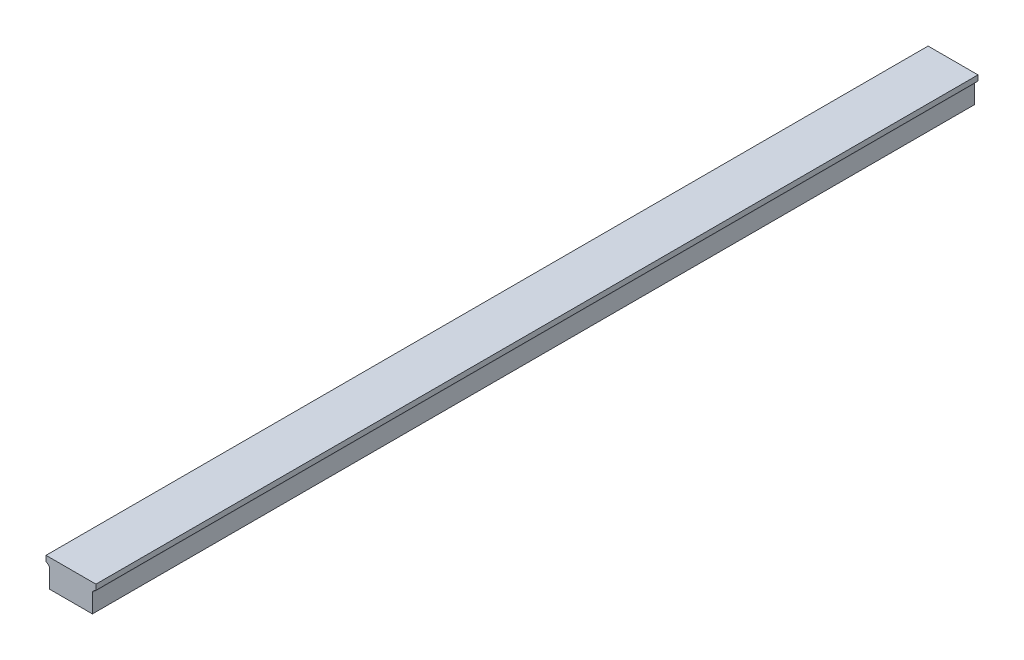
SolidWorks part; units mm, degrees
material "PET"
ref_plane "Front Plane" through (0, 0, 0) normal (0, 0, 1) x (1, 0, 0)
ref_plane "Top Plane" through (0, 0, 0) normal (0, 1, 0) x (1, 0, 0)
ref_plane "Right Plane" through (0, 0, 0) normal (1, 0, 0) x (0, 0, -1)
sketch "Sketch10" plane through (0, 0, 0) normal (0, 0, 1) x (1, 0, 0)
  line L0 (-0.9755, 4.9039) -> (-1.2681, 6.3751)
  line L1 (1.2681, 6.3751) -> (0.9755, 4.9039)
  line L2 (2.7779, 4.1573) -> (3.6112, 5.4046)
  line L3 (5.4046, 3.6112) -> (4.1573, 2.7779)
  line L4 (4.9039, 0.9755) -> (6.3751, 1.2681)
  line L5 (6.3751, -1.2681) -> (4.9039, -0.9755)
  line L6 (4.1573, -2.7779) -> (5.4046, -3.6112)
  line L7 (3.6112, -5.4046) -> (2.7779, -4.1573)
  line L8 (0.9755, -4.9039) -> (1.2681, -6.3751)
  line L9 (-1.2681, -6.3751) -> (-0.9755, -4.9039)
  line L10 (-2.7779, -4.1573) -> (-3.6112, -5.4046)
  line L11 (-5.4046, -3.6112) -> (-4.1573, -2.7779)
  line L12 (-4.9039, -0.9755) -> (-6.3751, -1.2681)
  line L13 (-6.3751, 1.2681) -> (-4.9039, 0.9755)
  line L14 (-4.1573, 2.7779) -> (-5.4046, 3.6112)
  line L15 (-3.6112, 5.4046) -> (-2.7779, 4.1573)
  line L16 (22.5, -6.3) -> (22.5, -19.5)
  line L17 (22, -5.8) -> (21, -5.8)
  line L18 (21, -5.8) -> (21, -5.5)
  line L19 (20.5, -5) -> (17.525, -5)
  line L20 (17.025, -5.5) -> (17.025, -9.55)
  line L21 (16.525, -10.05) -> (11.7571, -10.05)
  line L22 (11.4036, -9.9036) -> (6.6582, -5.1582)
  line L23 (11.4036, 9.9036) -> (6.6582, 5.1582)
  line L24 (17.025, 10.05) -> (11.7571, 10.05)
  line L25 (17.025, 5.5) -> (17.025, 10.05)
  line L26 (20.5, 5) -> (17.525, 5)
  line L27 (21, 5.8) -> (21, 5.5)
  line L28 (22, 5.8) -> (21, 5.8)
  line L29 (22.5, 19.5) -> (22.5, 6.3)
  line L30 (6.3, 22.5) -> (19.5, 22.5)
  line L31 (5.8, 22) -> (5.8, 21)
  line L32 (5.8, 21) -> (5.5, 21)
  line L33 (5, 20.5) -> (5, 17.525)
  line L34 (5.5, 17.025) -> (9.55, 17.025)
  line L35 (10.05, 16.525) -> (10.05, 11.7571)
  line L36 (9.9036, 11.4036) -> (5.1582, 6.6582)
  line L37 (-9.9036, 11.4036) -> (-5.1582, 6.6582)
  line L38 (-10.05, 16.525) -> (-10.05, 11.7571)
  line L39 (-5.5, 17.025) -> (-9.55, 17.025)
  line L40 (-5, 20.5) -> (-5, 17.525)
  line L41 (-5.8, 21) -> (-5.5, 21)
  line L42 (-5.8, 22) -> (-5.8, 21)
  line L43 (-19.5, 22.5) -> (-6.3, 22.5)
  line L44 (-22.5, 6.3) -> (-22.5, 19.5)
  line L45 (-22, 5.8) -> (-21, 5.8)
  line L46 (-21, 5.8) -> (-21, 5.5)
  line L47 (-20.5, 5) -> (-17.525, 5)
  line L48 (-17.025, 5.5) -> (-17.025, 9.55)
  line L49 (-16.525, 10.05) -> (-11.7571, 10.05)
  line L50 (-11.4036, 9.9036) -> (-6.6582, 5.1582)
  line L51 (-11.4036, -9.9036) -> (-6.6582, -5.1582)
  line L52 (-16.525, -10.05) -> (-11.7571, -10.05)
  line L53 (-17.025, -5.5) -> (-17.025, -9.55)
  line L54 (-20.5, -5) -> (-17.525, -5)
  line L55 (-21, -5.8) -> (-21, -5.5)
  line L56 (-22, -5.8) -> (-21, -5.8)
  line L57 (-22.5, -19.5) -> (-22.5, -6.3)
  line L58 (-6.3, -22.5) -> (-19.5, -22.5)
  line L59 (-5.8, -22) -> (-5.8, -21)
  line L60 (-5.8, -21) -> (-5.5, -21)
  line L61 (-5, -20.5) -> (-5, -17.525)
  line L62 (-5.5, -17.025) -> (-9.55, -17.025)
  line L63 (-10.05, -16.525) -> (-10.05, -11.7571)
  line L64 (-9.9036, -11.4036) -> (-5.1582, -6.6582)
  line L65 (9.9036, -11.4036) -> (5.1582, -6.6582)
  line L66 (10.05, -16.525) -> (10.05, -11.7571)
  line L67 (5.5, -17.025) -> (9.55, -17.025)
  line L68 (5, -20.5) -> (5, -17.525)
  line L69 (5.8, -21) -> (5.5, -21)
  line L70 (5.8, -22) -> (5.8, -21)
  line L71 (19.5, -22.5) -> (6.3, -22.5)
  line L72 (-18.025, 11.55) -> (-12.05, 11.55)
  line L73 (-18.525, 8.5375) -> (-18.525, 11.05)
  line L74 (-21, 8.5375) -> (-21, 19.5)
  line L75 (-19.5, 21) -> (-8.5375, 21)
  line L76 (-8.5375, 18.525) -> (-11.05, 18.525)
  line L77 (-11.55, 18.025) -> (-11.55, 12.05)
  line L78 (11.55, 18.025) -> (11.55, 12.05)
  line L79 (8.5375, 18.525) -> (11.05, 18.525)
  line L80 (8.5375, 21) -> (19.5, 21)
  line L81 (21, 19.5) -> (21, 8.5375)
  line L82 (18.525, 8.5375) -> (18.525, 11.05)
  line L83 (18.025, 11.55) -> (12.05, 11.55)
  line L84 (18.025, -11.55) -> (12.05, -11.55)
  line L85 (18.525, -8.5375) -> (18.525, -11.05)
  line L86 (21, -8.5375) -> (21, -19.5)
  line L87 (19.5, -21) -> (8.5375, -21)
  line L88 (8.5375, -18.525) -> (11.05, -18.525)
  line L89 (11.55, -18.025) -> (11.55, -12.05)
  line L90 (-11.55, -18.025) -> (-11.55, -12.05)
  line L91 (-8.5375, -18.525) -> (-11.05, -18.525)
  line L92 (-8.5375, -21) -> (-19.5, -21)
  line L93 (-21, -19.5) -> (-21, -8.5375)
  line L94 (-18.525, -8.5375) -> (-18.525, -11.55)
  line L95 (-18.525, -11.55) -> (-12.05, -11.55)
  line L96 (-22.5, 19.5) -> (-22.5, 24.5)
  line L97 (-22.5, 24.5) -> (24.5, 24.5)
  line L98 (24.5, 24.5) -> (24.5, -22.5)
  line L99 (24.5, -22.5) -> (19.5, -22.5)
  line L100 (8, 6.5) -> (8, -6.5)
  line L101 (-6.5, 8) -> (6.5, 8)
  arc A0 (0.9755, 4.9039) -> (-0.9755, 4.9039) centre (0, 0) ccw
  arc A1 (3.6112, 5.4046) -> (1.2681, 6.3751) centre (0, 0) ccw
  arc A2 (4.1573, 2.7779) -> (2.7779, 4.1573) centre (0, 0) ccw
  arc A3 (6.3751, 1.2681) -> (5.4046, 3.6112) centre (0, 0) ccw
  arc A4 (4.9039, -0.9755) -> (4.9039, 0.9755) centre (0, 0) ccw
  arc A5 (5.4046, -3.6112) -> (6.3751, -1.2681) centre (0, 0) ccw
  arc A6 (2.7779, -4.1573) -> (4.1573, -2.7779) centre (0, 0) ccw
  arc A7 (1.2681, -6.3751) -> (3.6112, -5.4046) centre (0, 0) ccw
  arc A8 (-0.9755, -4.9039) -> (0.9755, -4.9039) centre (0, 0) ccw
  arc A9 (-3.6112, -5.4046) -> (-1.2681, -6.3751) centre (0, 0) ccw
  arc A10 (-4.1573, -2.7779) -> (-2.7779, -4.1573) centre (0, 0) ccw
  arc A11 (-6.3751, -1.2681) -> (-5.4046, -3.6112) centre (0, 0) ccw
  arc A12 (-4.9039, 0.9755) -> (-4.9039, -0.9755) centre (0, 0) ccw
  arc A13 (-5.4046, 3.6112) -> (-6.3751, 1.2681) centre (0, 0) ccw
  arc A14 (-2.7779, 4.1573) -> (-4.1573, 2.7779) centre (0, 0) ccw
  arc A15 (-1.2681, 6.3751) -> (-3.6112, 5.4046) centre (0, 0) ccw
  arc A16 (22.5, -6.3) -> (22, -5.8) centre (22, -6.3) ccw
  arc A17 (21, -5.5) -> (20.5, -5) centre (20.5, -5.5) ccw
  arc A18 (17.525, -5) -> (17.025, -5.5) centre (17.525, -5.5) ccw
  arc A19 (16.525, -10.05) -> (17.025, -9.55) centre (16.525, -9.55) ccw
  arc A20 (11.4036, -9.9036) -> (11.7571, -10.05) centre (11.7571, -9.55) ccw
  arc A21 (6.5993, -4.522) -> (6.6582, -5.1582) centre (7.0118, -4.8047) ccw
  arc A22 (6.5993, -4.522) -> (6.5993, 4.522) centre (0, 0) ccw
  arc A23 (6.6582, 5.1582) -> (6.5993, 4.522) centre (7.0118, 4.8047) ccw
  arc A24 (11.7571, 10.05) -> (11.4036, 9.9036) centre (11.7571, 9.55) ccw
  arc A25 (17.025, 5.5) -> (17.525, 5) centre (17.525, 5.5) ccw
  arc A26 (20.5, 5) -> (21, 5.5) centre (20.5, 5.5) ccw
  arc A27 (22, 5.8) -> (22.5, 6.3) centre (22, 6.3) ccw
  arc A28 (22.5, 19.5) -> (19.5, 22.5) centre (19.5, 19.5) ccw
  arc A29 (6.3, 22.5) -> (5.8, 22) centre (6.3, 22) ccw
  arc A30 (5.5, 21) -> (5, 20.5) centre (5.5, 20.5) ccw
  arc A31 (5, 17.525) -> (5.5, 17.025) centre (5.5, 17.525) ccw
  arc A32 (10.05, 16.525) -> (9.55, 17.025) centre (9.55, 16.525) ccw
  arc A33 (9.9036, 11.4036) -> (10.05, 11.7571) centre (9.55, 11.7571) ccw
  arc A34 (4.522, 6.5993) -> (5.1582, 6.6582) centre (4.8047, 7.0118) ccw
  arc A35 (4.522, 6.5993) -> (-4.522, 6.5993) centre (0, 0) ccw
  arc A36 (-5.1582, 6.6582) -> (-4.522, 6.5993) centre (-4.8047, 7.0118) ccw
  arc A37 (-10.05, 11.7571) -> (-9.9036, 11.4036) centre (-9.55, 11.7571) ccw
  arc A38 (-9.55, 17.025) -> (-10.05, 16.525) centre (-9.55, 16.525) ccw
  arc A39 (-5.5, 17.025) -> (-5, 17.525) centre (-5.5, 17.525) ccw
  arc A40 (-5, 20.5) -> (-5.5, 21) centre (-5.5, 20.5) ccw
  arc A41 (-5.8, 22) -> (-6.3, 22.5) centre (-6.3, 22) ccw
  arc A42 (-19.5, 22.5) -> (-22.5, 19.5) centre (-19.5, 19.5) ccw
  arc A43 (-22.5, 6.3) -> (-22, 5.8) centre (-22, 6.3) ccw
  arc A44 (-21, 5.5) -> (-20.5, 5) centre (-20.5, 5.5) ccw
  arc A45 (-17.525, 5) -> (-17.025, 5.5) centre (-17.525, 5.5) ccw
  arc A46 (-16.525, 10.05) -> (-17.025, 9.55) centre (-16.525, 9.55) ccw
  arc A47 (-11.4036, 9.9036) -> (-11.7571, 10.05) centre (-11.7571, 9.55) ccw
  arc A48 (-6.5993, 4.522) -> (-6.6582, 5.1582) centre (-7.0118, 4.8047) ccw
  arc A49 (-6.5993, 4.522) -> (-6.5993, -4.522) centre (0, 0) ccw
  arc A50 (-6.6582, -5.1582) -> (-6.5993, -4.522) centre (-7.0118, -4.8047) ccw
  arc A51 (-11.7571, -10.05) -> (-11.4036, -9.9036) centre (-11.7571, -9.55) ccw
  arc A52 (-17.025, -9.55) -> (-16.525, -10.05) centre (-16.525, -9.55) ccw
  arc A53 (-17.025, -5.5) -> (-17.525, -5) centre (-17.525, -5.5) ccw
  arc A54 (-20.5, -5) -> (-21, -5.5) centre (-20.5, -5.5) ccw
  arc A55 (-22, -5.8) -> (-22.5, -6.3) centre (-22, -6.3) ccw
  arc A56 (-22.5, -19.5) -> (-19.5, -22.5) centre (-19.5, -19.5) ccw
  arc A57 (-6.3, -22.5) -> (-5.8, -22) centre (-6.3, -22) ccw
  arc A58 (-5.5, -21) -> (-5, -20.5) centre (-5.5, -20.5) ccw
  arc A59 (-5, -17.525) -> (-5.5, -17.025) centre (-5.5, -17.525) ccw
  arc A60 (-10.05, -16.525) -> (-9.55, -17.025) centre (-9.55, -16.525) ccw
  arc A61 (-9.9036, -11.4036) -> (-10.05, -11.7571) centre (-9.55, -11.7571) ccw
  arc A62 (-4.522, -6.5993) -> (-5.1582, -6.6582) centre (-4.8047, -7.0118) ccw
  arc A63 (-4.522, -6.5993) -> (4.522, -6.5993) centre (0, 0) ccw
  arc A64 (5.1582, -6.6582) -> (4.522, -6.5993) centre (4.8047, -7.0118) ccw
  arc A65 (10.05, -11.7571) -> (9.9036, -11.4036) centre (9.55, -11.7571) ccw
  arc A66 (9.55, -17.025) -> (10.05, -16.525) centre (9.55, -16.525) ccw
  arc A67 (5.5, -17.025) -> (5, -17.525) centre (5.5, -17.525) ccw
  arc A68 (5, -20.5) -> (5.5, -21) centre (5.5, -20.5) ccw
  arc A69 (5.8, -22) -> (6.3, -22.5) centre (6.3, -22) ccw
  arc A70 (19.5, -22.5) -> (22.5, -19.5) centre (19.5, -19.5) ccw
  arc A71 (-18.025, 11.55) -> (-18.525, 11.05) centre (-18.025, 11.05) ccw
  arc A72 (-21, 8.5375) -> (-18.525, 8.5375) centre (-19.7625, 8.5375) ccw
  arc A73 (-19.5, 21) -> (-21, 19.5) centre (-19.5, 19.5) ccw
  arc A74 (-8.5375, 18.525) -> (-8.5375, 21) centre (-8.5375, 19.7625) ccw
  arc A75 (-11.05, 18.525) -> (-11.55, 18.025) centre (-11.05, 18.025) ccw
  arc A76 (-12.05, 11.55) -> (-11.55, 12.05) centre (-12.05, 12.05) ccw
  arc A77 (11.55, 18.025) -> (11.05, 18.525) centre (11.05, 18.025) ccw
  arc A78 (8.5375, 21) -> (8.5375, 18.525) centre (8.5375, 19.7625) ccw
  arc A79 (21, 19.5) -> (19.5, 21) centre (19.5, 19.5) ccw
  arc A80 (18.525, 8.5375) -> (21, 8.5375) centre (19.7625, 8.5375) ccw
  arc A81 (18.525, 11.05) -> (18.025, 11.55) centre (18.025, 11.05) ccw
  arc A82 (11.55, 12.05) -> (12.05, 11.55) centre (12.05, 12.05) ccw
  arc A83 (18.025, -11.55) -> (18.525, -11.05) centre (18.025, -11.05) ccw
  arc A84 (21, -8.5375) -> (18.525, -8.5375) centre (19.7625, -8.5375) ccw
  arc A85 (19.5, -21) -> (21, -19.5) centre (19.5, -19.5) ccw
  arc A86 (8.5375, -18.525) -> (8.5375, -21) centre (8.5375, -19.7625) ccw
  arc A87 (11.05, -18.525) -> (11.55, -18.025) centre (11.05, -18.025) ccw
  arc A88 (12.05, -11.55) -> (11.55, -12.05) centre (12.05, -12.05) ccw
  arc A89 (-11.55, -18.025) -> (-11.05, -18.525) centre (-11.05, -18.025) ccw
  arc A90 (-8.5375, -21) -> (-8.5375, -18.525) centre (-8.5375, -19.7625) ccw
  arc A91 (-21, -19.5) -> (-19.5, -21) centre (-19.5, -19.5) ccw
  arc A92 (-18.525, -8.5375) -> (-21, -8.5375) centre (-19.7625, -8.5375) ccw
  arc A93 (-11.55, -12.05) -> (-12.05, -11.55) centre (-12.05, -12.05) ccw
  point P267 (8, 0)
  point P270 (0, 8)
  dimension "D1" = 45
  dimension "D2" = 45
  dimension "D3" = 47
extrude "Y-Rail Slot" add sketch "Sketch10" along normal mid plane 90 contours A70 L99 L98 L97 L96 A42 L43 A41 L42 L41 A40 L40 A39 L39 A38 L38 A37 L37 L101 L36 A33 L35 A32 L34 A31 L33 A30 L32 L31 A29 L30 A28 L29 A27 L28 L27 A26 L26 A25 L25 L24 A24 L23 L100 L22 A20 L21 A19 L20 region at (22.8236, -5.4764, 0)
sketch "Sketch12" plane through (0, 0, -45) normal (0, 0, -1) x (-1, 0, 0)
  line L30 (-22.5, -19.5) -> (-22.5, -6.3)
  line L42 (-22.5, -19.5) -> (-22.5, -6.3)
  line L44 (-22, -5.8) -> (-21, -5.8)
  line L46 (-22, -5.8) -> (-21, -5.8)
  line L48 (-21, -5.8) -> (-21, -5.5)
  line L50 (-21, -5.8) -> (-21, -5.5)
  line L52 (-20.5, -5) -> (-17.525, -5)
  line L54 (-20.5, -5) -> (-17.525, -5)
  line L56 (-17.025, -5.5) -> (-17.025, -9.55)
  line L109 (-17.025, -5.5) -> (-17.025, -9.55)
  line L122 (-16.525, -10.05) -> (-11.7571, -10.05)
  line L136 (-16.525, -10.05) -> (-11.7571, -10.05)
  line L146 (-11.4036, -9.9036) -> (-8, -6.5)
  line L150 (-11.4036, -9.9036) -> (-8, -6.5)
  line L154 (-8, -6.5) -> (-8, 6.5)
  line L158 (22.5, 19.5) -> (22.5, 24.5)
  line L159 (22.5, 19.5) -> (22.5, 24.5)
  line L160 (22.5, 24.5) -> (-24.5, 24.5)
  line L161 (22.5, 24.5) -> (-24.5, 24.5)
  line L162 (-24.5, 24.5) -> (-24.5, -22.5)
  line L163 (-24.5, 24.5) -> (-24.5, -22.5)
  line L164 (-24.5, -22.5) -> (-19.5, -22.5)
  line L165 (-24.5, -22.5) -> (-19.5, -22.5)
  line L166 (-8, -6.5) -> (-8, 6.5)
  line L168 (-8, 6.5) -> (-11.4036, 9.9036)
  line L170 (-8, 6.5) -> (-11.4036, 9.9036)
  line L172 (-11.7571, 10.05) -> (-17.025, 10.05)
  line L174 (-11.7571, 10.05) -> (-17.025, 10.05)
  line L176 (-17.025, 10.05) -> (-17.025, 5.5)
  line L178 (-17.025, 10.05) -> (-17.025, 5.5)
  line L180 (-17.525, 5) -> (-20.5, 5)
  line L182 (-17.525, 5) -> (-20.5, 5)
  line L184 (-21, 5.5) -> (-21, 5.8)
  line L186 (-21, 5.5) -> (-21, 5.8)
  line L188 (-21, 5.8) -> (-22, 5.8)
  line L190 (-21, 5.8) -> (-22, 5.8)
  line L192 (-22.5, 6.3) -> (-22.5, 19.5)
  line L194 (-22.5, 6.3) -> (-22.5, 19.5)
  line L196 (-19.5, 22.5) -> (-6.3, 22.5)
  line L197 (-19.5, 22.5) -> (-6.3, 22.5)
  line L198 (-5.8, 22) -> (-5.8, 21)
  line L199 (-5.8, 22) -> (-5.8, 21)
  line L200 (-5.8, 21) -> (-5.5, 21)
  line L201 (-5.8, 21) -> (-5.5, 21)
  line L202 (-5, 20.5) -> (-5, 17.525)
  line L203 (-5, 20.5) -> (-5, 17.525)
  line L204 (-5.5, 17.025) -> (-9.55, 17.025)
  line L205 (-5.5, 17.025) -> (-9.55, 17.025)
  line L206 (-10.05, 16.525) -> (-10.05, 11.7571)
  line L207 (-10.05, 16.525) -> (-10.05, 11.7571)
  line L208 (-9.9036, 11.4036) -> (-6.5, 8)
  line L209 (-9.9036, 11.4036) -> (-6.5, 8)
  line L210 (-6.5, 8) -> (6.5, 8)
  line L211 (-6.5, 8) -> (6.5, 8)
  line L212 (6.5, 8) -> (9.9036, 11.4036)
  line L213 (6.5, 8) -> (9.9036, 11.4036)
  line L214 (10.05, 11.7571) -> (10.05, 16.525)
  line L215 (10.05, 11.7571) -> (10.05, 16.525)
  line L216 (9.55, 17.025) -> (5.5, 17.025)
  line L217 (9.55, 17.025) -> (5.5, 17.025)
  line L218 (5, 17.525) -> (5, 20.5)
  line L219 (5, 17.525) -> (5, 20.5)
  line L220 (5.5, 21) -> (5.8, 21)
  line L221 (5.5, 21) -> (5.8, 21)
  line L222 (5.8, 21) -> (5.8, 22)
  line L223 (5.8, 21) -> (5.8, 22)
  line L224 (6.3, 22.5) -> (19.5, 22.5)
  line L225 (6.3, 22.5) -> (19.5, 22.5)
  arc A20 (-22.5, -19.5) -> (-19.5, -22.5) centre (-19.5, -19.5) ccw
  arc A29 (-22.5, -19.5) -> (-19.5, -22.5) centre (-19.5, -19.5) ccw
  arc A31 (-22, -5.8) -> (-22.5, -6.3) centre (-22, -6.3) ccw
  arc A33 (-22, -5.8) -> (-22.5, -6.3) centre (-22, -6.3) ccw
  arc A35 (-20.5, -5) -> (-21, -5.5) centre (-20.5, -5.5) ccw
  arc A37 (-20.5, -5) -> (-21, -5.5) centre (-20.5, -5.5) ccw
  arc A76 (-17.025, -5.5) -> (-17.525, -5) centre (-17.525, -5.5) ccw
  arc A90 (-17.025, -5.5) -> (-17.525, -5) centre (-17.525, -5.5) ccw
  arc A98 (-17.025, -9.55) -> (-16.525, -10.05) centre (-16.525, -9.55) ccw
  arc A102 (-17.025, -9.55) -> (-16.525, -10.05) centre (-16.525, -9.55) ccw
  arc A106 (-11.7571, -10.05) -> (-11.4036, -9.9036) centre (-11.7571, -9.55) ccw
  arc A110 (-11.7571, -10.05) -> (-11.4036, -9.9036) centre (-11.7571, -9.55) ccw
  arc A112 (-11.4036, 9.9036) -> (-11.7571, 10.05) centre (-11.7571, 9.55) ccw
  arc A114 (-11.4036, 9.9036) -> (-11.7571, 10.05) centre (-11.7571, 9.55) ccw
  arc A116 (-17.525, 5) -> (-17.025, 5.5) centre (-17.525, 5.5) ccw
  arc A118 (-17.525, 5) -> (-17.025, 5.5) centre (-17.525, 5.5) ccw
  arc A120 (-21, 5.5) -> (-20.5, 5) centre (-20.5, 5.5) ccw
  arc A122 (-21, 5.5) -> (-20.5, 5) centre (-20.5, 5.5) ccw
  arc A124 (-22.5, 6.3) -> (-22, 5.8) centre (-22, 6.3) ccw
  arc A126 (-22.5, 6.3) -> (-22, 5.8) centre (-22, 6.3) ccw
  arc A128 (-19.5, 22.5) -> (-22.5, 19.5) centre (-19.5, 19.5) ccw
  arc A130 (-19.5, 22.5) -> (-22.5, 19.5) centre (-19.5, 19.5) ccw
  arc A132 (-5.8, 22) -> (-6.3, 22.5) centre (-6.3, 22) ccw
  arc A133 (-5.8, 22) -> (-6.3, 22.5) centre (-6.3, 22) ccw
  arc A134 (-5, 20.5) -> (-5.5, 21) centre (-5.5, 20.5) ccw
  arc A135 (-5, 20.5) -> (-5.5, 21) centre (-5.5, 20.5) ccw
  arc A136 (-5.5, 17.025) -> (-5, 17.525) centre (-5.5, 17.525) ccw
  arc A137 (-5.5, 17.025) -> (-5, 17.525) centre (-5.5, 17.525) ccw
  arc A138 (-9.55, 17.025) -> (-10.05, 16.525) centre (-9.55, 16.525) ccw
  arc A139 (-9.55, 17.025) -> (-10.05, 16.525) centre (-9.55, 16.525) ccw
  arc A140 (-10.05, 11.7571) -> (-9.9036, 11.4036) centre (-9.55, 11.7571) ccw
  arc A141 (-10.05, 11.7571) -> (-9.9036, 11.4036) centre (-9.55, 11.7571) ccw
  arc A142 (9.9036, 11.4036) -> (10.05, 11.7571) centre (9.55, 11.7571) ccw
  arc A143 (9.9036, 11.4036) -> (10.05, 11.7571) centre (9.55, 11.7571) ccw
  arc A144 (10.05, 16.525) -> (9.55, 17.025) centre (9.55, 16.525) ccw
  arc A145 (10.05, 16.525) -> (9.55, 17.025) centre (9.55, 16.525) ccw
  arc A146 (5, 17.525) -> (5.5, 17.025) centre (5.5, 17.525) ccw
  arc A147 (5, 17.525) -> (5.5, 17.025) centre (5.5, 17.525) ccw
  arc A148 (5.5, 21) -> (5, 20.5) centre (5.5, 20.5) ccw
  arc A149 (5.5, 21) -> (5, 20.5) centre (5.5, 20.5) ccw
  arc A150 (6.3, 22.5) -> (5.8, 22) centre (6.3, 22) ccw
  arc A151 (6.3, 22.5) -> (5.8, 22) centre (6.3, 22) ccw
  arc A152 (22.5, 19.5) -> (19.5, 22.5) centre (19.5, 19.5) ccw
  arc A153 (22.5, 19.5) -> (19.5, 22.5) centre (19.5, 19.5) ccw
  dimension "D1" = 0
extrude "Y-Rail cont." add sketch "Sketch12" along normal blind 2
sketch "Sketch17" plane through (0, 24.5, 0) normal (0, 1, 0) x (1, 0, 0)
  line L0 (19.5, -45) -> (24.5, -45)
  line L1 (24.5, -45) -> (24.5, 2)
  line L2 (24.5, 2) -> (-22.5, 2)
  line L3 (-22.5, 2) -> (-22.5, -3)
  line L4 (-19.5, 0) -> (-6.3, 0)
  line L5 (-5.8, -0.5) -> (-5.8, -1.5)
  line L6 (-5.8, -1.5) -> (-5.5, -1.5)
  line L7 (-5, -2) -> (-5, -4.975)
  line L8 (-5.5, -5.475) -> (-9.55, -5.475)
  line L9 (-10.05, -5.975) -> (-10.05, -10.7429)
  line L10 (-9.9036, -11.0964) -> (-6.5, -14.5)
  line L11 (-6.5, -14.5) -> (6.5, -14.5)
  line L12 (6.5, -14.5) -> (9.9036, -11.0964)
  line L13 (10.05, -10.7429) -> (10.05, -5.975)
  line L14 (9.55, -5.475) -> (5.5, -5.475)
  line L15 (5, -4.975) -> (5, -2)
  line L16 (5.5, -1.5) -> (5.8, -1.5)
  line L17 (5.8, -1.5) -> (5.8, -0.5)
  line L18 (6.3, 0) -> (19.5, 0)
  line L19 (22.5, -3) -> (22.5, -16.2)
  line L20 (22, -16.7) -> (21, -16.7)
  line L21 (21, -16.7) -> (21, -17)
  line L22 (20.5, -17.5) -> (17.525, -17.5)
  line L23 (17.025, -17) -> (17.025, -12.45)
  line L24 (17.025, -12.45) -> (11.7571, -12.45)
  line L25 (11.4036, -12.5964) -> (8, -16)
  line L26 (8, -16) -> (8, -29)
  line L27 (8, -29) -> (11.4036, -32.4036)
  line L28 (11.7571, -32.55) -> (16.525, -32.55)
  line L29 (17.025, -32.05) -> (17.025, -28)
  line L30 (17.525, -27.5) -> (20.5, -27.5)
  line L31 (21, -28) -> (21, -28.3)
  line L32 (21, -28.3) -> (22, -28.3)
  line L33 (22.5, -28.8) -> (22.5, -42)
  arc A0 (19.5, -45) -> (22.5, -42) centre (19.5, -42) ccw
  arc A1 (-19.5, 0) -> (-22.5, -3) centre (-19.5, -3) ccw
  arc A2 (-5.8, -0.5) -> (-6.3, 0) centre (-6.3, -0.5) ccw
  arc A3 (-5, -2) -> (-5.5, -1.5) centre (-5.5, -2) ccw
  arc A4 (-5.5, -5.475) -> (-5, -4.975) centre (-5.5, -4.975) ccw
  arc A5 (-9.55, -5.475) -> (-10.05, -5.975) centre (-9.55, -5.975) ccw
  arc A6 (-10.05, -10.7429) -> (-9.9036, -11.0964) centre (-9.55, -10.7429) ccw
  arc A7 (9.9036, -11.0964) -> (10.05, -10.7429) centre (9.55, -10.7429) ccw
  arc A8 (10.05, -5.975) -> (9.55, -5.475) centre (9.55, -5.975) ccw
  arc A9 (5, -4.975) -> (5.5, -5.475) centre (5.5, -4.975) ccw
  arc A10 (5.5, -1.5) -> (5, -2) centre (5.5, -2) ccw
  arc A11 (6.3, 0) -> (5.8, -0.5) centre (6.3, -0.5) ccw
  arc A12 (22.5, -3) -> (19.5, 0) centre (19.5, -3) ccw
  arc A13 (22, -16.7) -> (22.5, -16.2) centre (22, -16.2) ccw
  arc A14 (20.5, -17.5) -> (21, -17) centre (20.5, -17) ccw
  arc A15 (17.025, -17) -> (17.525, -17.5) centre (17.525, -17) ccw
  arc A16 (11.7571, -12.45) -> (11.4036, -12.5964) centre (11.7571, -12.95) ccw
  arc A17 (11.4036, -32.4036) -> (11.7571, -32.55) centre (11.7571, -32.05) ccw
  arc A18 (16.525, -32.55) -> (17.025, -32.05) centre (16.525, -32.05) ccw
  arc A19 (17.525, -27.5) -> (17.025, -28) centre (17.525, -28) ccw
  arc A20 (21, -28) -> (20.5, -27.5) centre (20.5, -28) ccw
  arc A21 (22.5, -28.8) -> (22, -28.3) centre (22, -28.8) ccw
extrude "Z-Rail Slot" add sketch "Sketch17" along normal blind 45
sketch "Sketch11" plane through (24.5, 0, 0) normal (1, 0, 0) x (0, 0, -1)
  line L0 (-5.95, -19.5) -> (5.95, -19.5)
  line L1 (-10.95, -11.7571) -> (-10.95, -14.5)
  line L2 (-11.8642, -10.0145) -> (-11.5358, -10.3429)
  line L3 (-12.45, 8.6003) -> (-12.45, -8.6003)
  line L4 (-11.8642, 10.0145) -> (-11.5358, 10.3429)
  line L5 (-10.95, 11.7571) -> (-10.95, 14.5)
  line L6 (-5.95, 19.5) -> (5.95, 19.5)
  line L7 (10.95, 11.7571) -> (10.95, 14.5)
  line L8 (11.8642, 10.0145) -> (11.5358, 10.3429)
  line L9 (12.45, 8.6003) -> (12.45, -8.6003)
  line L10 (11.8642, -10.0145) -> (11.5358, -10.3429)
  line L11 (10.95, -11.7571) -> (10.95, -14.5)
  line L12 (-27.4039, -0.9755) -> (-28.8751, -1.2681)
  line L13 (-28.8751, 1.2681) -> (-27.4039, 0.9755)
  line L14 (-26.6573, 2.7779) -> (-27.9046, 3.6112)
  line L15 (-26.1112, 5.4046) -> (-25.2779, 4.1573)
  line L16 (-23.4755, 4.9039) -> (-23.7681, 6.3751)
  line L17 (-21.2319, 6.3751) -> (-21.5245, 4.9039)
  line L18 (-19.7221, 4.1573) -> (-18.8888, 5.4046)
  line L19 (-17.0954, 3.6112) -> (-18.3427, 2.7779)
  line L20 (-17.5961, 0.9755) -> (-16.1249, 1.2681)
  line L21 (-16.1249, -1.2681) -> (-17.5961, -0.9755)
  line L22 (-18.3427, -2.7779) -> (-17.0954, -3.6112)
  line L23 (-18.8888, -5.4046) -> (-19.7221, -4.1573)
  line L24 (-21.5245, -4.9039) -> (-21.2319, -6.3751)
  line L25 (-23.7681, -6.3751) -> (-23.4755, -4.9039)
  line L26 (-25.2779, -4.1573) -> (-26.1112, -5.4046)
  line L27 (-27.9046, -3.6112) -> (-26.6573, -2.7779)
  line L28 (-40.525, 11.55) -> (-34.55, 11.55)
  line L29 (-41.025, 8.5375) -> (-41.025, 11.05)
  line L30 (-43.5, 8.5375) -> (-43.5, 19.5)
  line L31 (-42, 21) -> (-31.0375, 21)
  line L32 (-31.0375, 18.525) -> (-33.55, 18.525)
  line L33 (-34.05, 18.025) -> (-34.05, 12.05)
  line L34 (-34.05, -18.025) -> (-34.05, -12.05)
  line L35 (-31.0375, -18.525) -> (-33.55, -18.525)
  line L36 (-31.0375, -21) -> (-42, -21)
  line L37 (-43.5, -19.5) -> (-43.5, -8.5375)
  line L38 (-41.025, -8.5375) -> (-41.025, -11.05)
  line L39 (-40.525, -11.55) -> (-34.55, -11.55)
  line L40 (16.7, 22) -> (16.7, 21)
  line L41 (16.2, 22.5) -> (7.8, 22.5)
  line L42 (7.8, 22.5) -> (7.8, 21.5)
  line L43 (-7.3, 21) -> (7.3, 21)
  line L44 (-7.8, 22.5) -> (-7.8, 21.5)
  line L45 (-16.2, 22.5) -> (-7.8, 22.5)
  line L46 (-16.7, 22) -> (-16.7, 21)
  line L47 (-16.7, 21) -> (-17, 21)
  line L48 (-17.5, 20.5) -> (-17.5, 17.525)
  line L49 (-17, 17.025) -> (-12.95, 17.025)
  line L50 (-12.45, 16.525) -> (-12.45, 11.7571)
  line L51 (-12.5964, 11.4036) -> (-17.3418, 6.6582)
  line L52 (-32.4036, 11.4036) -> (-27.6582, 6.6582)
  line L53 (-32.55, 17.025) -> (-32.55, 11.7571)
  line L54 (-28, 17.025) -> (-32.55, 17.025)
  line L55 (-27.5, 20.5) -> (-27.5, 17.525)
  line L56 (-28.3, 21) -> (-28, 21)
  line L57 (-28.3, 22) -> (-28.3, 21)
  line L58 (-42, 22.5) -> (-28.8, 22.5)
  line L59 (-45, 6.3) -> (-45, 19.5)
  line L60 (-44.5, 5.8) -> (-43.5, 5.8)
  line L61 (-43.5, 5.8) -> (-43.5, 5.5)
  line L62 (-43, 5) -> (-40.025, 5)
  line L63 (-39.525, 5.5) -> (-39.525, 9.55)
  line L64 (-39.025, 10.05) -> (-34.2571, 10.05)
  line L65 (-33.9036, 9.9036) -> (-29.1582, 5.1582)
  line L66 (-33.9036, -9.9036) -> (-29.1582, -5.1582)
  line L67 (-39.025, -10.05) -> (-34.2571, -10.05)
  line L68 (-39.525, -5.5) -> (-39.525, -9.55)
  line L69 (-43, -5) -> (-40.025, -5)
  line L70 (-43.5, -5.8) -> (-43.5, -5.5)
  line L71 (-44.5, -5.8) -> (-43.5, -5.8)
  line L72 (-45, -19.5) -> (-45, -6.3)
  line L73 (-28.8, -22.5) -> (-42, -22.5)
  line L74 (-28.3, -22) -> (-28.3, -21)
  line L75 (-28.3, -21) -> (-28, -21)
  line L76 (-27.5, -20.5) -> (-27.5, -17.525)
  line L77 (-28, -17.025) -> (-32.05, -17.025)
  line L78 (-32.55, -16.525) -> (-32.55, -11.7571)
  line L79 (-32.4036, -11.4036) -> (-27.6582, -6.6582)
  line L80 (-12.5964, -11.4036) -> (-17.3418, -6.6582)
  line L81 (-12.45, -16.525) -> (-12.45, -11.7571)
  line L82 (-17, -17.025) -> (-12.95, -17.025)
  line L83 (-17.5, -20.5) -> (-17.5, -17.525)
  line L84 (-16.7, -21) -> (-17, -21)
  line L85 (-16.7, -22) -> (-16.7, -21)
  line L86 (-7.8, -22.5) -> (-16.2, -22.5)
  line L87 (-7.8, -22.5) -> (-7.8, -21.5)
  line L88 (-7.3, -21) -> (7.3, -21)
  line L89 (7.8, -22.5) -> (7.8, -21.5)
  line L90 (7.8, -22.5) -> (16.2, -22.5)
  line L91 (16.7, -22) -> (16.7, -21)
  line L92 (16.7, -21) -> (17, -21)
  line L93 (17.5, -20.5) -> (17.5, -17.525)
  line L94 (17, -17.025) -> (12.95, -17.025)
  line L95 (12.45, -16.525) -> (12.45, -11.7571)
  line L96 (12.5964, -11.4036) -> (17.3418, -6.6582)
  line L97 (32.4036, -11.4036) -> (27.6582, -6.6582)
  line L98 (32.55, -16.525) -> (32.55, -11.7571)
  line L99 (28, -17.025) -> (32.05, -17.025)
  line L100 (27.5, -20.5) -> (27.5, -17.525)
  line L101 (28.3, -21) -> (28, -21)
  line L102 (28.3, -22) -> (28.3, -21)
  line L103 (28.8, -22.5) -> (42, -22.5)
  line L104 (45, -19.5) -> (45, -6.3)
  line L105 (44.5, -5.8) -> (43.5, -5.8)
  line L106 (43.5, -5.8) -> (43.5, -5.5)
  line L107 (43, -5) -> (40.025, -5)
  line L108 (39.525, -5.5) -> (39.525, -9.55)
  line L109 (39.025, -10.05) -> (34.2571, -10.05)
  line L110 (33.9036, -9.9036) -> (29.1582, -5.1582)
  line L111 (33.9036, 9.9036) -> (29.1582, 5.1582)
  line L112 (39.025, 10.05) -> (34.2571, 10.05)
  line L113 (39.525, 5.5) -> (39.525, 9.55)
  line L114 (43, 5) -> (40.025, 5)
  line L115 (43.5, 5.8) -> (43.5, 5.5)
  line L116 (44.5, 5.8) -> (43.5, 5.8)
  line L117 (45, 6.3) -> (45, 19.5)
  line L118 (42, 22.5) -> (28.8, 22.5)
  line L119 (28.3, 22) -> (28.3, 21)
  line L120 (28.3, 21) -> (28, 21)
  line L121 (27.5, 20.5) -> (27.5, 17.525)
  line L122 (28, 17.025) -> (32.55, 17.025)
  line L123 (32.55, 17.025) -> (32.55, 11.7571)
  line L124 (32.4036, 11.4036) -> (27.6582, 6.6582)
  line L125 (12.5964, 11.4036) -> (17.3418, 6.6582)
  line L126 (12.45, 16.525) -> (12.45, 11.7571)
  line L127 (17, 17.025) -> (12.95, 17.025)
  line L128 (17.5, 20.5) -> (17.5, 17.525)
  line L129 (16.7, 21) -> (17, 21)
  line L130 (41.025, 8.5375) -> (41.025, 11.05)
  line L131 (40.525, 11.55) -> (34.55, 11.55)
  line L132 (34.05, 18.025) -> (34.05, 12.05)
  line L133 (31.0375, 18.525) -> (33.55, 18.525)
  line L134 (42, 21) -> (31.0375, 21)
  line L135 (43.5, 8.5375) -> (43.5, 19.5)
  line L136 (31.0375, -18.525) -> (33.55, -18.525)
  line L137 (34.05, -18.025) -> (34.05, -12.05)
  line L138 (40.525, -11.55) -> (34.55, -11.55)
  line L139 (41.025, -8.5375) -> (41.025, -11.05)
  line L140 (43.5, -19.5) -> (43.5, -8.5375)
  line L141 (31.0375, -21) -> (42, -21)
  line L142 (27.9046, -3.6112) -> (26.6573, -2.7779)
  line L143 (25.2779, -4.1573) -> (26.1112, -5.4046)
  line L144 (23.7681, -6.3751) -> (23.4755, -4.9039)
  line L145 (21.5245, -4.9039) -> (21.2319, -6.3751)
  line L146 (18.8888, -5.4046) -> (19.7221, -4.1573)
  line L147 (18.3427, -2.7779) -> (17.0954, -3.6112)
  line L148 (16.1249, -1.2681) -> (17.5961, -0.9755)
  line L149 (17.5961, 0.9755) -> (16.1249, 1.2681)
  line L150 (17.0954, 3.6112) -> (18.3427, 2.7779)
  line L151 (19.7221, 4.1573) -> (18.8888, 5.4046)
  line L152 (21.2319, 6.3751) -> (21.5245, 4.9039)
  line L153 (23.4755, 4.9039) -> (23.7681, 6.3751)
  line L154 (26.1112, 5.4046) -> (25.2779, 4.1573)
  line L155 (26.6573, 2.7779) -> (27.9046, 3.6112)
  line L156 (28.8751, 1.2681) -> (27.4039, 0.9755)
  line L157 (27.4039, -0.9755) -> (28.8751, -1.2681)
  line L158 (-45, 69.5) -> (-45, -22.5) construction
  line L160 (-45, 19.5) -> (-45, 6.3)
  line L162 (-45, -6.3) -> (-45, -19.5)
  line L163 (47, 24.5) -> (47, -22.5)
  line L164 (-45, -22.5) -> (47, -22.5) construction
  line L165 (47, -22.5) -> (42, -22.5)
  line L166 (47, 24.5) -> (-45, 24.5)
  line L167 (-45, 24.5) -> (-45, 19.5)
  line L168 (-29, 8) -> (-16, 8)
  line L169 (16, 8) -> (29, 8)
  line L170 (30.5, 6.5) -> (30.5, -6.5)
  arc A0 (5.95, -19.5) -> (10.95, -14.5) centre (5.95, -14.5) ccw
  arc A1 (-10.95, -14.5) -> (-5.95, -19.5) centre (-5.95, -14.5) ccw
  arc A2 (-10.95, -11.7571) -> (-11.5358, -10.3429) centre (-12.95, -11.7571) ccw
  arc A3 (-12.45, -8.6003) -> (-11.8642, -10.0145) centre (-10.45, -8.6003) ccw
  arc A4 (-11.8642, 10.0145) -> (-12.45, 8.6003) centre (-10.45, 8.6003) ccw
  arc A5 (-11.5358, 10.3429) -> (-10.95, 11.7571) centre (-12.95, 11.7571) ccw
  arc A6 (-5.95, 19.5) -> (-10.95, 14.5) centre (-5.95, 14.5) ccw
  arc A7 (10.95, 14.5) -> (5.95, 19.5) centre (5.95, 14.5) ccw
  arc A8 (10.95, 11.7571) -> (11.5358, 10.3429) centre (12.95, 11.7571) ccw
  arc A9 (12.45, 8.6003) -> (11.8642, 10.0145) centre (10.45, 8.6003) ccw
  arc A10 (11.8642, -10.0145) -> (12.45, -8.6003) centre (10.45, -8.6003) ccw
  arc A11 (11.5358, -10.3429) -> (10.95, -11.7571) centre (12.95, -11.7571) ccw
  arc A12 (-27.4039, 0.9755) -> (-27.4039, -0.9755) centre (-22.5, 0) ccw
  arc A13 (-27.9046, 3.6112) -> (-28.8751, 1.2681) centre (-22.5, 0) ccw
  arc A14 (-25.2779, 4.1573) -> (-26.6573, 2.7779) centre (-22.5, 0) ccw
  arc A15 (-23.7681, 6.3751) -> (-26.1112, 5.4046) centre (-22.5, 0) ccw
  arc A16 (-21.5245, 4.9039) -> (-23.4755, 4.9039) centre (-22.5, 0) ccw
  arc A17 (-18.8888, 5.4046) -> (-21.2319, 6.3751) centre (-22.5, 0) ccw
  arc A18 (-18.3427, 2.7779) -> (-19.7221, 4.1573) centre (-22.5, 0) ccw
  arc A19 (-16.1249, 1.2681) -> (-17.0954, 3.6112) centre (-22.5, 0) ccw
  arc A20 (-17.5961, -0.9755) -> (-17.5961, 0.9755) centre (-22.5, 0) ccw
  arc A21 (-17.0954, -3.6112) -> (-16.1249, -1.2681) centre (-22.5, 0) ccw
  arc A22 (-19.7221, -4.1573) -> (-18.3427, -2.7779) centre (-22.5, 0) ccw
  arc A23 (-21.2319, -6.3751) -> (-18.8888, -5.4046) centre (-22.5, 0) ccw
  arc A24 (-23.4755, -4.9039) -> (-21.5245, -4.9039) centre (-22.5, 0) ccw
  arc A25 (-26.1112, -5.4046) -> (-23.7681, -6.3751) centre (-22.5, 0) ccw
  arc A26 (-26.6573, -2.7779) -> (-25.2779, -4.1573) centre (-22.5, 0) ccw
  arc A27 (-28.8751, -1.2681) -> (-27.9046, -3.6112) centre (-22.5, 0) ccw
  arc A28 (-40.525, 11.55) -> (-41.025, 11.05) centre (-40.525, 11.05) ccw
  arc A29 (-43.5, 8.5375) -> (-41.025, 8.5375) centre (-42.2625, 8.5375) ccw
  arc A30 (-42, 21) -> (-43.5, 19.5) centre (-42, 19.5) ccw
  arc A31 (-31.0375, 18.525) -> (-31.0375, 21) centre (-31.0375, 19.7625) ccw
  arc A32 (-33.55, 18.525) -> (-34.05, 18.025) centre (-33.55, 18.025) ccw
  arc A33 (-34.55, 11.55) -> (-34.05, 12.05) centre (-34.55, 12.05) ccw
  arc A34 (-34.05, -18.025) -> (-33.55, -18.525) centre (-33.55, -18.025) ccw
  arc A35 (-31.0375, -21) -> (-31.0375, -18.525) centre (-31.0375, -19.7625) ccw
  arc A36 (-43.5, -19.5) -> (-42, -21) centre (-42, -19.5) ccw
  arc A37 (-41.025, -8.5375) -> (-43.5, -8.5375) centre (-42.2625, -8.5375) ccw
  arc A38 (-41.025, -11.05) -> (-40.525, -11.55) centre (-40.525, -11.05) ccw
  arc A39 (-34.05, -12.05) -> (-34.55, -11.55) centre (-34.55, -12.05) ccw
  arc A40 (16.7, 22) -> (16.2, 22.5) centre (16.2, 22) ccw
  arc A41 (7.3, 21) -> (7.8, 21.5) centre (7.3, 21.5) ccw
  arc A42 (-7.8, 21.5) -> (-7.3, 21) centre (-7.3, 21.5) ccw
  arc A43 (-16.2, 22.5) -> (-16.7, 22) centre (-16.2, 22) ccw
  arc A44 (-17, 21) -> (-17.5, 20.5) centre (-17, 20.5) ccw
  arc A45 (-17.5, 17.525) -> (-17, 17.025) centre (-17, 17.525) ccw
  arc A46 (-12.45, 16.525) -> (-12.95, 17.025) centre (-12.95, 16.525) ccw
  arc A47 (-12.5964, 11.4036) -> (-12.45, 11.7571) centre (-12.95, 11.7571) ccw
  arc A48 (-17.978, 6.5993) -> (-17.3418, 6.6582) centre (-17.6953, 7.0118) ccw
  arc A49 (-17.978, 6.5993) -> (-27.022, 6.5993) centre (-22.5, 0) ccw
  arc A50 (-27.6582, 6.6582) -> (-27.022, 6.5993) centre (-27.3047, 7.0118) ccw
  arc A51 (-32.55, 11.7571) -> (-32.4036, 11.4036) centre (-32.05, 11.7571) ccw
  arc A52 (-28, 17.025) -> (-27.5, 17.525) centre (-28, 17.525) ccw
  arc A53 (-27.5, 20.5) -> (-28, 21) centre (-28, 20.5) ccw
  arc A54 (-28.3, 22) -> (-28.8, 22.5) centre (-28.8, 22) ccw
  arc A55 (-42, 22.5) -> (-45, 19.5) centre (-42, 19.5) ccw
  arc A56 (-45, 6.3) -> (-44.5, 5.8) centre (-44.5, 6.3) ccw
  arc A57 (-43.5, 5.5) -> (-43, 5) centre (-43, 5.5) ccw
  arc A58 (-40.025, 5) -> (-39.525, 5.5) centre (-40.025, 5.5) ccw
  arc A59 (-39.025, 10.05) -> (-39.525, 9.55) centre (-39.025, 9.55) ccw
  arc A60 (-33.9036, 9.9036) -> (-34.2571, 10.05) centre (-34.2571, 9.55) ccw
  arc A61 (-29.0993, 4.522) -> (-29.1582, 5.1582) centre (-29.5118, 4.8047) ccw
  arc A62 (-29.0993, 4.522) -> (-29.0993, -4.522) centre (-22.5, 0) ccw
  arc A63 (-29.1582, -5.1582) -> (-29.0993, -4.522) centre (-29.5118, -4.8047) ccw
  arc A64 (-34.2571, -10.05) -> (-33.9036, -9.9036) centre (-34.2571, -9.55) ccw
  arc A65 (-39.525, -9.55) -> (-39.025, -10.05) centre (-39.025, -9.55) ccw
  arc A66 (-39.525, -5.5) -> (-40.025, -5) centre (-40.025, -5.5) ccw
  arc A67 (-43, -5) -> (-43.5, -5.5) centre (-43, -5.5) ccw
  arc A68 (-44.5, -5.8) -> (-45, -6.3) centre (-44.5, -6.3) ccw
  arc A69 (-45, -19.5) -> (-42, -22.5) centre (-42, -19.5) ccw
  arc A70 (-28.8, -22.5) -> (-28.3, -22) centre (-28.8, -22) ccw
  arc A71 (-28, -21) -> (-27.5, -20.5) centre (-28, -20.5) ccw
  arc A72 (-27.5, -17.525) -> (-28, -17.025) centre (-28, -17.525) ccw
  arc A73 (-32.55, -16.525) -> (-32.05, -17.025) centre (-32.05, -16.525) ccw
  arc A74 (-32.4036, -11.4036) -> (-32.55, -11.7571) centre (-32.05, -11.7571) ccw
  arc A75 (-27.022, -6.5993) -> (-27.6582, -6.6582) centre (-27.3047, -7.0118) ccw
  arc A76 (-27.022, -6.5993) -> (-17.978, -6.5993) centre (-22.5, 0) ccw
  arc A77 (-17.3418, -6.6582) -> (-17.978, -6.5993) centre (-17.6953, -7.0118) ccw
  arc A78 (-12.45, -11.7571) -> (-12.5964, -11.4036) centre (-12.95, -11.7571) ccw
  arc A79 (-12.95, -17.025) -> (-12.45, -16.525) centre (-12.95, -16.525) ccw
  arc A80 (-17, -17.025) -> (-17.5, -17.525) centre (-17, -17.525) ccw
  arc A81 (-17.5, -20.5) -> (-17, -21) centre (-17, -20.5) ccw
  arc A82 (-16.7, -22) -> (-16.2, -22.5) centre (-16.2, -22) ccw
  arc A83 (-7.3, -21) -> (-7.8, -21.5) centre (-7.3, -21.5) ccw
  arc A84 (7.8, -21.5) -> (7.3, -21) centre (7.3, -21.5) ccw
  arc A85 (16.2, -22.5) -> (16.7, -22) centre (16.2, -22) ccw
  arc A86 (17, -21) -> (17.5, -20.5) centre (17, -20.5) ccw
  arc A87 (17.5, -17.525) -> (17, -17.025) centre (17, -17.525) ccw
  arc A88 (12.45, -16.525) -> (12.95, -17.025) centre (12.95, -16.525) ccw
  arc A89 (12.5964, -11.4036) -> (12.45, -11.7571) centre (12.95, -11.7571) ccw
  arc A90 (17.978, -6.5993) -> (17.3418, -6.6582) centre (17.6953, -7.0118) ccw
  arc A91 (17.978, -6.5993) -> (27.022, -6.5993) centre (22.5, 0) ccw
  arc A92 (27.6582, -6.6582) -> (27.022, -6.5993) centre (27.3047, -7.0118) ccw
  arc A93 (32.55, -11.7571) -> (32.4036, -11.4036) centre (32.05, -11.7571) ccw
  arc A94 (32.05, -17.025) -> (32.55, -16.525) centre (32.05, -16.525) ccw
  arc A95 (28, -17.025) -> (27.5, -17.525) centre (28, -17.525) ccw
  arc A96 (27.5, -20.5) -> (28, -21) centre (28, -20.5) ccw
  arc A97 (28.3, -22) -> (28.8, -22.5) centre (28.8, -22) ccw
  arc A98 (42, -22.5) -> (45, -19.5) centre (42, -19.5) ccw
  arc A99 (45, -6.3) -> (44.5, -5.8) centre (44.5, -6.3) ccw
  arc A100 (43.5, -5.5) -> (43, -5) centre (43, -5.5) ccw
  arc A101 (40.025, -5) -> (39.525, -5.5) centre (40.025, -5.5) ccw
  arc A102 (39.025, -10.05) -> (39.525, -9.55) centre (39.025, -9.55) ccw
  arc A103 (33.9036, -9.9036) -> (34.2571, -10.05) centre (34.2571, -9.55) ccw
  arc A104 (29.0993, -4.522) -> (29.1582, -5.1582) centre (29.5118, -4.8047) ccw
  arc A105 (29.0993, -4.522) -> (29.0993, 4.522) centre (22.5, 0) ccw
  arc A106 (29.1582, 5.1582) -> (29.0993, 4.522) centre (29.5118, 4.8047) ccw
  arc A107 (34.2571, 10.05) -> (33.9036, 9.9036) centre (34.2571, 9.55) ccw
  arc A108 (39.525, 9.55) -> (39.025, 10.05) centre (39.025, 9.55) ccw
  arc A109 (39.525, 5.5) -> (40.025, 5) centre (40.025, 5.5) ccw
  arc A110 (43, 5) -> (43.5, 5.5) centre (43, 5.5) ccw
  arc A111 (44.5, 5.8) -> (45, 6.3) centre (44.5, 6.3) ccw
  arc A112 (45, 19.5) -> (42, 22.5) centre (42, 19.5) ccw
  arc A113 (28.8, 22.5) -> (28.3, 22) centre (28.8, 22) ccw
  arc A114 (28, 21) -> (27.5, 20.5) centre (28, 20.5) ccw
  arc A115 (27.5, 17.525) -> (28, 17.025) centre (28, 17.525) ccw
  arc A116 (32.4036, 11.4036) -> (32.55, 11.7571) centre (32.05, 11.7571) ccw
  arc A117 (27.022, 6.5993) -> (27.6582, 6.6582) centre (27.3047, 7.0118) ccw
  arc A118 (27.022, 6.5993) -> (17.978, 6.5993) centre (22.5, 0) ccw
  arc A119 (17.3418, 6.6582) -> (17.978, 6.5993) centre (17.6953, 7.0118) ccw
  arc A120 (12.45, 11.7571) -> (12.5964, 11.4036) centre (12.95, 11.7571) ccw
  arc A121 (12.95, 17.025) -> (12.45, 16.525) centre (12.95, 16.525) ccw
  arc A122 (17, 17.025) -> (17.5, 17.525) centre (17, 17.525) ccw
  arc A123 (17.5, 20.5) -> (17, 21) centre (17, 20.5) ccw
  arc A124 (41.025, 11.05) -> (40.525, 11.55) centre (40.525, 11.05) ccw
  arc A125 (34.05, 12.05) -> (34.55, 11.55) centre (34.55, 12.05) ccw
  arc A126 (34.05, 18.025) -> (33.55, 18.525) centre (33.55, 18.025) ccw
  arc A127 (31.0375, 21) -> (31.0375, 18.525) centre (31.0375, 19.7625) ccw
  arc A128 (43.5, 19.5) -> (42, 21) centre (42, 19.5) ccw
  arc A129 (41.025, 8.5375) -> (43.5, 8.5375) centre (42.2625, 8.5375) ccw
  arc A130 (33.55, -18.525) -> (34.05, -18.025) centre (33.55, -18.025) ccw
  arc A131 (34.55, -11.55) -> (34.05, -12.05) centre (34.55, -12.05) ccw
  arc A132 (40.525, -11.55) -> (41.025, -11.05) centre (40.525, -11.05) ccw
  arc A133 (43.5, -8.5375) -> (41.025, -8.5375) centre (42.2625, -8.5375) ccw
  arc A134 (42, -21) -> (43.5, -19.5) centre (42, -19.5) ccw
  arc A135 (31.0375, -18.525) -> (31.0375, -21) centre (31.0375, -19.7625) ccw
  arc A136 (27.9046, -3.6112) -> (28.8751, -1.2681) centre (22.5, 0) ccw
  arc A137 (25.2779, -4.1573) -> (26.6573, -2.7779) centre (22.5, 0) ccw
  arc A138 (23.7681, -6.3751) -> (26.1112, -5.4046) centre (22.5, 0) ccw
  arc A139 (21.5245, -4.9039) -> (23.4755, -4.9039) centre (22.5, 0) ccw
  arc A140 (18.8888, -5.4046) -> (21.2319, -6.3751) centre (22.5, 0) ccw
  arc A141 (18.3427, -2.7779) -> (19.7221, -4.1573) centre (22.5, 0) ccw
  arc A142 (16.1249, -1.2681) -> (17.0954, -3.6112) centre (22.5, 0) ccw
  arc A143 (17.5961, 0.9755) -> (17.5961, -0.9755) centre (22.5, 0) ccw
  arc A144 (17.0954, 3.6112) -> (16.1249, 1.2681) centre (22.5, 0) ccw
  arc A145 (19.7221, 4.1573) -> (18.3427, 2.7779) centre (22.5, 0) ccw
  arc A146 (21.2319, 6.3751) -> (18.8888, 5.4046) centre (22.5, 0) ccw
  arc A147 (23.4755, 4.9039) -> (21.5245, 4.9039) centre (22.5, 0) ccw
  arc A148 (26.1112, 5.4046) -> (23.7681, 6.3751) centre (22.5, 0) ccw
  arc A149 (26.6573, 2.7779) -> (25.2779, 4.1573) centre (22.5, 0) ccw
  arc A150 (28.8751, 1.2681) -> (27.9046, 3.6112) centre (22.5, 0) ccw
  arc A151 (27.4039, -0.9755) -> (27.4039, 0.9755) centre (22.5, 0) ccw
  point P429 (-22.5, 8)
  point P432 (22.5, 8)
  point P435 (30.5, 0)
  dimension "D1" = 2
extrude "X-Rail Slot" add sketch "Sketch11" along normal blind 45 contours A123 L128 A122 L127 A121 L126 A120 L125 A119 A118 A117 L124 A116 L123 L122 A115 L121 A114 L120 L119 A113 L118 A112 L117 A111 L116 L115 A110 L114 A109 L113 A108 L112 A107 L111 A106 A105 A104 L110 A103 L109 A102 L108 A101 L107 A100 L106 L105 A99 L104 A98 region at (24.5, 11.6744, -13.0299)
sketch "Sketch20" plane through (0, 69.5, 0) normal (0, 1, 0) x (1, 0, 0)
  line L34 (19.5, -45) -> (24.5, -45)
  line L35 (24.5, -45) -> (24.5, 2)
  line L36 (24.5, 2) -> (-22.5, 2)
  line L37 (-22.5, 2) -> (-22.5, -3)
  line L38 (-19.5, 0) -> (-6.3, 0)
  line L39 (-5.8, -0.5) -> (-5.8, -1.5)
  line L40 (-5.8, -1.5) -> (-5.5, -1.5)
  line L41 (-5, -2) -> (-5, -4.975)
  line L42 (-5.5, -5.475) -> (-9.55, -5.475)
  line L43 (-10.05, -5.975) -> (-10.05, -10.7429)
  line L44 (-9.9036, -11.0964) -> (-6.5, -14.5)
  line L45 (-6.5, -14.5) -> (6.5, -14.5)
  line L46 (6.5, -14.5) -> (9.9036, -11.0964)
  line L47 (10.05, -10.7429) -> (10.05, -5.975)
  line L48 (9.55, -5.475) -> (5.5, -5.475)
  line L49 (5, -4.975) -> (5, -2)
  line L50 (5.5, -1.5) -> (5.8, -1.5)
  line L51 (5.8, -1.5) -> (5.8, -0.5)
  line L52 (6.3, 0) -> (19.5, 0)
  line L53 (22.5, -3) -> (22.5, -16.2)
  line L54 (22, -16.7) -> (21, -16.7)
  line L55 (21, -16.7) -> (21, -17)
  line L56 (20.5, -17.5) -> (17.525, -17.5)
  line L57 (17.025, -17) -> (17.025, -12.45)
  line L58 (17.025, -12.45) -> (11.7571, -12.45)
  line L59 (11.4036, -12.5964) -> (8, -16)
  line L60 (8, -16) -> (8, -29)
  line L61 (8, -29) -> (11.4036, -32.4036)
  line L62 (11.7571, -32.55) -> (16.525, -32.55)
  line L63 (17.025, -32.05) -> (17.025, -28)
  line L64 (17.525, -27.5) -> (20.5, -27.5)
  line L65 (21, -28) -> (21, -28.3)
  line L66 (21, -28.3) -> (22, -28.3)
  line L67 (22.5, -28.8) -> (22.5, -42)
  line L72 (-19.5, 0) -> (-6.3, 0)
  line L73 (-5.8, -0.5) -> (-5.8, -1.5)
  line L74 (-5.8, -1.5) -> (-5.5, -1.5)
  line L75 (-5, -2) -> (-5, -4.975)
  line L76 (-5.5, -5.475) -> (-9.55, -5.475)
  line L77 (-10.05, -5.975) -> (-10.05, -10.7429)
  line L78 (-9.9036, -11.0964) -> (-6.5, -14.5)
  line L79 (-6.5, -14.5) -> (6.5, -14.5)
  line L80 (6.5, -14.5) -> (9.9036, -11.0964)
  line L81 (10.05, -10.7429) -> (10.05, -5.975)
  line L82 (9.55, -5.475) -> (5.5, -5.475)
  line L83 (5, -4.975) -> (5, -2)
  line L84 (5.5, -1.5) -> (5.8, -1.5)
  line L85 (5.8, -1.5) -> (5.8, -0.5)
  line L86 (6.3, 0) -> (19.5, 0)
  line L87 (22.5, -3) -> (22.5, -16.2)
  line L88 (22, -16.7) -> (21, -16.7)
  line L89 (21, -16.7) -> (21, -17)
  line L90 (20.5, -17.5) -> (17.525, -17.5)
  line L91 (17.025, -17) -> (17.025, -12.45)
  line L92 (17.025, -12.45) -> (11.7571, -12.45)
  line L93 (11.4036, -12.5964) -> (8, -16)
  line L94 (8, -16) -> (8, -29)
  line L95 (8, -29) -> (11.4036, -32.4036)
  line L96 (11.7571, -32.55) -> (16.525, -32.55)
  line L97 (17.025, -32.05) -> (17.025, -28)
  line L98 (17.525, -27.5) -> (20.5, -27.5)
  line L99 (21, -28) -> (21, -28.3)
  line L100 (21, -28.3) -> (22, -28.3)
  line L101 (22.5, -28.8) -> (22.5, -42)
  arc A22 (19.5, -45) -> (22.5, -42) centre (19.5, -42) ccw
  arc A23 (-19.5, 0) -> (-22.5, -3) centre (-19.5, -3) ccw
  arc A24 (-5.8, -0.5) -> (-6.3, 0) centre (-6.3, -0.5) ccw
  arc A25 (-5, -2) -> (-5.5, -1.5) centre (-5.5, -2) ccw
  arc A26 (-5.5, -5.475) -> (-5, -4.975) centre (-5.5, -4.975) ccw
  arc A27 (-9.55, -5.475) -> (-10.05, -5.975) centre (-9.55, -5.975) ccw
  arc A28 (-10.05, -10.7429) -> (-9.9036, -11.0964) centre (-9.55, -10.7429) ccw
  arc A29 (9.9036, -11.0964) -> (10.05, -10.7429) centre (9.55, -10.7429) ccw
  arc A30 (10.05, -5.975) -> (9.55, -5.475) centre (9.55, -5.975) ccw
  arc A31 (5, -4.975) -> (5.5, -5.475) centre (5.5, -4.975) ccw
  arc A32 (5.5, -1.5) -> (5, -2) centre (5.5, -2) ccw
  arc A33 (6.3, 0) -> (5.8, -0.5) centre (6.3, -0.5) ccw
  arc A34 (22.5, -3) -> (19.5, 0) centre (19.5, -3) ccw
  arc A35 (22, -16.7) -> (22.5, -16.2) centre (22, -16.2) ccw
  arc A36 (20.5, -17.5) -> (21, -17) centre (20.5, -17) ccw
  arc A37 (17.025, -17) -> (17.525, -17.5) centre (17.525, -17) ccw
  arc A38 (11.7571, -12.45) -> (11.4036, -12.5964) centre (11.7571, -12.95) ccw
  arc A39 (11.4036, -32.4036) -> (11.7571, -32.55) centre (11.7571, -32.05) ccw
  arc A40 (16.525, -32.55) -> (17.025, -32.05) centre (16.525, -32.05) ccw
  arc A41 (17.525, -27.5) -> (17.025, -28) centre (17.525, -28) ccw
  arc A42 (21, -28) -> (20.5, -27.5) centre (20.5, -28) ccw
  arc A43 (22.5, -28.8) -> (22, -28.3) centre (22, -28.8) ccw
  arc A44 (19.5, -45) -> (22.5, -42) centre (19.5, -42) ccw
  arc A45 (-19.5, 0) -> (-22.5, -3) centre (-19.5, -3) ccw
  arc A46 (-5.8, -0.5) -> (-6.3, 0) centre (-6.3, -0.5) ccw
  arc A47 (-5, -2) -> (-5.5, -1.5) centre (-5.5, -2) ccw
  arc A48 (-5.5, -5.475) -> (-5, -4.975) centre (-5.5, -4.975) ccw
  arc A49 (-9.55, -5.475) -> (-10.05, -5.975) centre (-9.55, -5.975) ccw
  arc A50 (-10.05, -10.7429) -> (-9.9036, -11.0964) centre (-9.55, -10.7429) ccw
  arc A51 (9.9036, -11.0964) -> (10.05, -10.7429) centre (9.55, -10.7429) ccw
  arc A52 (10.05, -5.975) -> (9.55, -5.475) centre (9.55, -5.975) ccw
  arc A53 (5, -4.975) -> (5.5, -5.475) centre (5.5, -4.975) ccw
  arc A54 (5.5, -1.5) -> (5, -2) centre (5.5, -2) ccw
  arc A55 (6.3, 0) -> (5.8, -0.5) centre (6.3, -0.5) ccw
  arc A56 (22.5, -3) -> (19.5, 0) centre (19.5, -3) ccw
  arc A57 (22, -16.7) -> (22.5, -16.2) centre (22, -16.2) ccw
  arc A58 (20.5, -17.5) -> (21, -17) centre (20.5, -17) ccw
  arc A59 (17.025, -17) -> (17.525, -17.5) centre (17.525, -17) ccw
  arc A60 (11.7571, -12.45) -> (11.4036, -12.5964) centre (11.7571, -12.95) ccw
  arc A61 (11.4036, -32.4036) -> (11.7571, -32.55) centre (11.7571, -32.05) ccw
  arc A62 (16.525, -32.55) -> (17.025, -32.05) centre (16.525, -32.05) ccw
  arc A63 (17.525, -27.5) -> (17.025, -28) centre (17.525, -28) ccw
  arc A64 (21, -28) -> (20.5, -27.5) centre (20.5, -28) ccw
  arc A65 (22.5, -28.8) -> (22, -28.3) centre (22, -28.8) ccw
  dimension "D1" = 0
extrude "Tolerance Cut Z" cut sketch "Sketch20" against normal up to surface (45 mm away) thin up to face at (7.7111, 24.5, 14.6597) thin type one direction wall 0.1
sketch "Sketch21" plane through (0, 0, 45) normal (0, 0, 1) x (1, 0, 0)
  line L40 (20.281, 69.5) -> (20.281, 24.5)
  line L41 (20.281, 24.5) -> (-22.5, 24.5)
  line L42 (-22.5, 24.5) -> (-22.5, 19.5)
  line L43 (-19.5, 22.5) -> (-6.3, 22.5)
  line L44 (-5.8, 22) -> (-5.8, 21)
  line L45 (-5.8, 21) -> (-5.5, 21)
  line L46 (-5, 20.5) -> (-5, 17.525)
  line L47 (-5.5, 17.025) -> (-9.55, 17.025)
  line L48 (-10.05, 16.525) -> (-10.05, 11.7571)
  line L49 (-9.9036, 11.4036) -> (-6.5, 8)
  line L50 (-6.5, 8) -> (6.5, 8)
  line L51 (6.5, 8) -> (9.9036, 11.4036)
  line L52 (10.05, 11.7571) -> (10.05, 16.525)
  line L53 (9.55, 17.025) -> (5.5, 17.025)
  line L54 (5, 17.525) -> (5, 20.5)
  line L55 (5.5, 21) -> (5.8, 21)
  line L56 (5.8, 21) -> (5.8, 22)
  line L57 (6.3, 22.5) -> (19.5, 22.5)
  line L58 (22.5, 19.5) -> (22.5, 6.3)
  line L59 (22, 5.8) -> (21, 5.8)
  line L60 (21, 5.8) -> (21, 5.5)
  line L61 (20.5, 5) -> (17.525, 5)
  line L62 (17.025, 5.5) -> (17.025, 10.05)
  line L63 (17.025, 10.05) -> (11.7571, 10.05)
  line L64 (11.4036, 9.9036) -> (8, 6.5)
  line L65 (8, 6.5) -> (8, -6.5)
  line L66 (8, -6.5) -> (11.4036, -9.9036)
  line L67 (11.7571, -10.05) -> (16.525, -10.05)
  line L68 (17.025, -9.55) -> (17.025, -5.5)
  line L69 (17.525, -5) -> (20.5, -5)
  line L70 (21, -5.5) -> (21, -5.8)
  line L71 (21, -5.8) -> (22, -5.8)
  line L72 (22.5, -6.3) -> (22.5, -19.5)
  line L73 (19.5, -22.5) -> (24.5, -22.5)
  line L74 (24.5, -22.5) -> (24.5, 19.5)
  line L75 (24.5, 19.5) -> (69.5, 19.5)
  line L76 (69.5, 19.5) -> (69.5, 24.5)
  line L77 (69.5, 24.5) -> (24.5, 24.5)
  line L78 (24.5, 24.5) -> (24.5, 69.5)
  line L79 (24.5, 69.5) -> (20.281, 69.5)
  line L83 (-19.5, 22.5) -> (-6.3, 22.5)
  line L84 (-5.8, 22) -> (-5.8, 21)
  line L85 (-5.8, 21) -> (-5.5, 21)
  line L86 (-5, 20.5) -> (-5, 17.525)
  line L87 (-5.5, 17.025) -> (-9.55, 17.025)
  line L88 (-10.05, 16.525) -> (-10.05, 11.7571)
  line L89 (-9.9036, 11.4036) -> (-6.5, 8)
  line L90 (-6.5, 8) -> (6.5, 8)
  line L91 (6.5, 8) -> (9.9036, 11.4036)
  line L92 (10.05, 11.7571) -> (10.05, 16.525)
  line L93 (9.55, 17.025) -> (5.5, 17.025)
  line L94 (5, 17.525) -> (5, 20.5)
  line L95 (5.5, 21) -> (5.8, 21)
  line L96 (5.8, 21) -> (5.8, 22)
  line L97 (6.3, 22.5) -> (19.5, 22.5)
  line L98 (22.5, 19.5) -> (22.5, 6.3)
  line L99 (22, 5.8) -> (21, 5.8)
  line L100 (21, 5.8) -> (21, 5.5)
  line L101 (20.5, 5) -> (17.525, 5)
  line L102 (17.025, 5.5) -> (17.025, 10.05)
  line L103 (17.025, 10.05) -> (11.7571, 10.05)
  line L104 (11.4036, 9.9036) -> (8, 6.5)
  line L105 (8, 6.5) -> (8, -6.5)
  line L106 (8, -6.5) -> (11.4036, -9.9036)
  line L107 (11.7571, -10.05) -> (16.525, -10.05)
  line L108 (17.025, -9.55) -> (17.025, -5.5)
  line L109 (17.525, -5) -> (20.5, -5)
  line L110 (21, -5.5) -> (21, -5.8)
  line L111 (21, -5.8) -> (22, -5.8)
  line L112 (22.5, -6.3) -> (22.5, -19.5)
  line L116 (69.5, 19.5) -> (69.5, 24.5)
  line L119 (24.5, 69.5) -> (20.281, 69.5)
  arc A22 (-19.5, 22.5) -> (-22.5, 19.5) centre (-19.5, 19.5) ccw
  arc A23 (-5.8, 22) -> (-6.3, 22.5) centre (-6.3, 22) ccw
  arc A24 (-5, 20.5) -> (-5.5, 21) centre (-5.5, 20.5) ccw
  arc A25 (-5.5, 17.025) -> (-5, 17.525) centre (-5.5, 17.525) ccw
  arc A26 (-9.55, 17.025) -> (-10.05, 16.525) centre (-9.55, 16.525) ccw
  arc A27 (-10.05, 11.7571) -> (-9.9036, 11.4036) centre (-9.55, 11.7571) ccw
  arc A28 (9.9036, 11.4036) -> (10.05, 11.7571) centre (9.55, 11.7571) ccw
  arc A29 (10.05, 16.525) -> (9.55, 17.025) centre (9.55, 16.525) ccw
  arc A30 (5, 17.525) -> (5.5, 17.025) centre (5.5, 17.525) ccw
  arc A31 (5.5, 21) -> (5, 20.5) centre (5.5, 20.5) ccw
  arc A32 (6.3, 22.5) -> (5.8, 22) centre (6.3, 22) ccw
  arc A33 (22.5, 19.5) -> (19.5, 22.5) centre (19.5, 19.5) ccw
  arc A34 (22, 5.8) -> (22.5, 6.3) centre (22, 6.3) ccw
  arc A35 (20.5, 5) -> (21, 5.5) centre (20.5, 5.5) ccw
  arc A36 (17.025, 5.5) -> (17.525, 5) centre (17.525, 5.5) ccw
  arc A37 (11.7571, 10.05) -> (11.4036, 9.9036) centre (11.7571, 9.55) ccw
  arc A38 (11.4036, -9.9036) -> (11.7571, -10.05) centre (11.7571, -9.55) ccw
  arc A39 (16.525, -10.05) -> (17.025, -9.55) centre (16.525, -9.55) ccw
  arc A40 (17.525, -5) -> (17.025, -5.5) centre (17.525, -5.5) ccw
  arc A41 (21, -5.5) -> (20.5, -5) centre (20.5, -5.5) ccw
  arc A42 (22.5, -6.3) -> (22, -5.8) centre (22, -6.3) ccw
  arc A43 (19.5, -22.5) -> (22.5, -19.5) centre (19.5, -19.5) ccw
  arc A44 (-19.5, 22.5) -> (-22.5, 19.5) centre (-19.5, 19.5) ccw
  arc A45 (-5.8, 22) -> (-6.3, 22.5) centre (-6.3, 22) ccw
  arc A46 (-5, 20.5) -> (-5.5, 21) centre (-5.5, 20.5) ccw
  arc A47 (-5.5, 17.025) -> (-5, 17.525) centre (-5.5, 17.525) ccw
  arc A48 (-9.55, 17.025) -> (-10.05, 16.525) centre (-9.55, 16.525) ccw
  arc A49 (-10.05, 11.7571) -> (-9.9036, 11.4036) centre (-9.55, 11.7571) ccw
  arc A50 (9.9036, 11.4036) -> (10.05, 11.7571) centre (9.55, 11.7571) ccw
  arc A51 (10.05, 16.525) -> (9.55, 17.025) centre (9.55, 16.525) ccw
  arc A52 (5, 17.525) -> (5.5, 17.025) centre (5.5, 17.525) ccw
  arc A53 (5.5, 21) -> (5, 20.5) centre (5.5, 20.5) ccw
  arc A54 (6.3, 22.5) -> (5.8, 22) centre (6.3, 22) ccw
  arc A55 (22.5, 19.5) -> (19.5, 22.5) centre (19.5, 19.5) ccw
  arc A56 (22, 5.8) -> (22.5, 6.3) centre (22, 6.3) ccw
  arc A57 (20.5, 5) -> (21, 5.5) centre (20.5, 5.5) ccw
  arc A58 (17.025, 5.5) -> (17.525, 5) centre (17.525, 5.5) ccw
  arc A59 (11.7571, 10.05) -> (11.4036, 9.9036) centre (11.7571, 9.55) ccw
  arc A60 (11.4036, -9.9036) -> (11.7571, -10.05) centre (11.7571, -9.55) ccw
  arc A61 (16.525, -10.05) -> (17.025, -9.55) centre (16.525, -9.55) ccw
  arc A62 (17.525, -5) -> (17.025, -5.5) centre (17.525, -5.5) ccw
  arc A63 (21, -5.5) -> (20.5, -5) centre (20.5, -5.5) ccw
  arc A64 (22.5, -6.3) -> (22, -5.8) centre (22, -6.3) ccw
  arc A65 (19.5, -22.5) -> (22.5, -19.5) centre (19.5, -19.5) ccw
  dimension "D1" = 0
extrude "Tolerance Cut Y" cut sketch "Sketch21" against normal through all thin thin type one direction wall 0.1
sketch "Sketch22" plane through (69.5, 0, 0) normal (1, 0, 0) x (0, 0, -1)
  line L52 (45, 19.5) -> (45, 6.3)
  line L53 (44.5, 5.8) -> (43.5, 5.8)
  line L54 (43.5, 5.8) -> (43.5, 5.5)
  line L55 (43, 5) -> (40.025, 5)
  line L56 (39.525, 5.5) -> (39.525, 9.55)
  line L57 (39.025, 10.05) -> (34.2571, 10.05)
  line L58 (33.9036, 9.9036) -> (30.5, 6.5)
  line L59 (30.5, 6.5) -> (30.5, -6.5)
  line L60 (30.5, -6.5) -> (33.9036, -9.9036)
  line L61 (34.2571, -10.05) -> (39.025, -10.05)
  line L62 (39.525, -9.55) -> (39.525, -5.5)
  line L63 (40.025, -5) -> (43, -5)
  line L64 (43.5, -5.5) -> (43.5, -5.8)
  line L65 (43.5, -5.8) -> (44.5, -5.8)
  line L66 (45, -6.3) -> (45, -19.5)
  line L67 (42, -22.5) -> (47, -22.5)
  line L68 (47, -22.5) -> (47, 24.5)
  line L69 (47, 24.5) -> (-45, 24.5)
  line L70 (-45, 24.5) -> (-45, 19.5)
  line L71 (-42, 22.5) -> (-28.8, 22.5)
  line L72 (-28.3, 22) -> (-28.3, 21)
  line L73 (-28.3, 21) -> (-28, 21)
  line L74 (-27.5, 20.5) -> (-27.5, 17.525)
  line L75 (-28, 17.025) -> (-32.55, 17.025)
  line L76 (-32.55, 17.025) -> (-32.55, 11.7571)
  line L77 (-32.4036, 11.4036) -> (-29, 8)
  line L78 (-29, 8) -> (-16, 8)
  line L79 (-16, 8) -> (-12.5964, 11.4036)
  line L80 (-12.45, 11.7571) -> (-12.45, 16.525)
  line L81 (-12.95, 17.025) -> (-17, 17.025)
  line L82 (-17.5, 17.525) -> (-17.5, 20.5)
  line L83 (-17, 21) -> (-16.7, 21)
  line L84 (-16.7, 21) -> (-16.7, 22)
  line L85 (-16.2, 22.5) -> (-7.8, 22.5)
  line L86 (-7.8, 22.5) -> (-7.8, 21.5)
  line L87 (-7.3, 21) -> (7.3, 21)
  line L88 (7.8, 21.5) -> (7.8, 22.5)
  line L89 (7.8, 22.5) -> (16.2, 22.5)
  line L90 (16.7, 22) -> (16.7, 21)
  line L91 (16.7, 21) -> (17, 21)
  line L92 (17.5, 20.5) -> (17.5, 17.525)
  line L93 (17, 17.025) -> (12.95, 17.025)
  line L94 (12.45, 16.525) -> (12.45, 11.7571)
  line L95 (12.5964, 11.4036) -> (16, 8)
  line L96 (16, 8) -> (29, 8)
  line L97 (29, 8) -> (32.4036, 11.4036)
  line L98 (32.55, 11.7571) -> (32.55, 17.025)
  line L99 (32.55, 17.025) -> (28, 17.025)
  line L100 (27.5, 17.525) -> (27.5, 20.5)
  line L101 (28, 21) -> (28.3, 21)
  line L102 (28.3, 21) -> (28.3, 22)
  line L103 (28.8, 22.5) -> (42, 22.5)
  line L104 (45, 19.5) -> (45, 6.3)
  line L105 (44.5, 5.8) -> (43.5, 5.8)
  line L106 (43.5, 5.8) -> (43.5, 5.5)
  line L107 (43, 5) -> (40.025, 5)
  line L108 (39.525, 5.5) -> (39.525, 9.55)
  line L109 (39.025, 10.05) -> (34.2571, 10.05)
  line L110 (33.9036, 9.9036) -> (30.5, 6.5)
  line L111 (30.5, 6.5) -> (30.5, -6.5)
  line L112 (30.5, -6.5) -> (33.9036, -9.9036)
  line L113 (34.2571, -10.05) -> (39.025, -10.05)
  line L114 (39.525, -9.55) -> (39.525, -5.5)
  line L115 (40.025, -5) -> (43, -5)
  line L116 (43.5, -5.5) -> (43.5, -5.8)
  line L117 (43.5, -5.8) -> (44.5, -5.8)
  line L118 (45, -6.3) -> (45, -19.5)
  line L123 (-42, 22.5) -> (-28.8, 22.5)
  line L124 (-28.3, 22) -> (-28.3, 21)
  line L125 (-28.3, 21) -> (-28, 21)
  line L126 (-27.5, 20.5) -> (-27.5, 17.525)
  line L127 (-28, 17.025) -> (-32.55, 17.025)
  line L128 (-32.55, 17.025) -> (-32.55, 11.7571)
  line L129 (-32.4036, 11.4036) -> (-29, 8)
  line L130 (-29, 8) -> (-16, 8)
  line L131 (-16, 8) -> (-12.5964, 11.4036)
  line L132 (-12.45, 11.7571) -> (-12.45, 16.525)
  line L133 (-12.95, 17.025) -> (-17, 17.025)
  line L134 (-17.5, 17.525) -> (-17.5, 20.5)
  line L135 (-17, 21) -> (-16.7, 21)
  line L136 (-16.7, 21) -> (-16.7, 22)
  line L137 (-16.2, 22.5) -> (-7.8, 22.5)
  line L138 (-7.8, 22.5) -> (-7.8, 21.5)
  line L139 (-7.3, 21) -> (7.3, 21)
  line L140 (7.8, 21.5) -> (7.8, 22.5)
  line L141 (7.8, 22.5) -> (16.2, 22.5)
  line L142 (16.7, 22) -> (16.7, 21)
  line L143 (16.7, 21) -> (17, 21)
  line L144 (17.5, 20.5) -> (17.5, 17.525)
  line L145 (17, 17.025) -> (12.95, 17.025)
  line L146 (12.45, 16.525) -> (12.45, 11.7571)
  line L147 (12.5964, 11.4036) -> (16, 8)
  line L148 (16, 8) -> (29, 8)
  line L149 (29, 8) -> (32.4036, 11.4036)
  line L150 (32.55, 11.7571) -> (32.55, 17.025)
  line L151 (32.55, 17.025) -> (28, 17.025)
  line L152 (27.5, 17.525) -> (27.5, 20.5)
  line L153 (28, 21) -> (28.3, 21)
  line L154 (28.3, 21) -> (28.3, 22)
  line L155 (28.8, 22.5) -> (42, 22.5)
  arc A33 (45, 19.5) -> (42, 22.5) centre (42, 19.5) ccw
  arc A34 (44.5, 5.8) -> (45, 6.3) centre (44.5, 6.3) ccw
  arc A35 (43, 5) -> (43.5, 5.5) centre (43, 5.5) ccw
  arc A36 (39.525, 5.5) -> (40.025, 5) centre (40.025, 5.5) ccw
  arc A37 (39.525, 9.55) -> (39.025, 10.05) centre (39.025, 9.55) ccw
  arc A38 (34.2571, 10.05) -> (33.9036, 9.9036) centre (34.2571, 9.55) ccw
  arc A39 (33.9036, -9.9036) -> (34.2571, -10.05) centre (34.2571, -9.55) ccw
  arc A40 (39.025, -10.05) -> (39.525, -9.55) centre (39.025, -9.55) ccw
  arc A41 (40.025, -5) -> (39.525, -5.5) centre (40.025, -5.5) ccw
  arc A42 (43.5, -5.5) -> (43, -5) centre (43, -5.5) ccw
  arc A43 (45, -6.3) -> (44.5, -5.8) centre (44.5, -6.3) ccw
  arc A44 (42, -22.5) -> (45, -19.5) centre (42, -19.5) ccw
  arc A45 (-42, 22.5) -> (-45, 19.5) centre (-42, 19.5) ccw
  arc A46 (-28.3, 22) -> (-28.8, 22.5) centre (-28.8, 22) ccw
  arc A47 (-27.5, 20.5) -> (-28, 21) centre (-28, 20.5) ccw
  arc A48 (-28, 17.025) -> (-27.5, 17.525) centre (-28, 17.525) ccw
  arc A49 (-32.55, 11.7571) -> (-32.4036, 11.4036) centre (-32.05, 11.7571) ccw
  arc A50 (-12.5964, 11.4036) -> (-12.45, 11.7571) centre (-12.95, 11.7571) ccw
  arc A51 (-12.45, 16.525) -> (-12.95, 17.025) centre (-12.95, 16.525) ccw
  arc A52 (-17.5, 17.525) -> (-17, 17.025) centre (-17, 17.525) ccw
  arc A53 (-17, 21) -> (-17.5, 20.5) centre (-17, 20.5) ccw
  arc A54 (-16.2, 22.5) -> (-16.7, 22) centre (-16.2, 22) ccw
  arc A55 (-7.8, 21.5) -> (-7.3, 21) centre (-7.3, 21.5) ccw
  arc A56 (7.3, 21) -> (7.8, 21.5) centre (7.3, 21.5) ccw
  arc A57 (16.7, 22) -> (16.2, 22.5) centre (16.2, 22) ccw
  arc A58 (17.5, 20.5) -> (17, 21) centre (17, 20.5) ccw
  arc A59 (17, 17.025) -> (17.5, 17.525) centre (17, 17.525) ccw
  arc A60 (12.95, 17.025) -> (12.45, 16.525) centre (12.95, 16.525) ccw
  arc A61 (12.45, 11.7571) -> (12.5964, 11.4036) centre (12.95, 11.7571) ccw
  arc A62 (32.4036, 11.4036) -> (32.55, 11.7571) centre (32.05, 11.7571) ccw
  arc A63 (27.5, 17.525) -> (28, 17.025) centre (28, 17.525) ccw
  arc A64 (28, 21) -> (27.5, 20.5) centre (28, 20.5) ccw
  arc A65 (28.8, 22.5) -> (28.3, 22) centre (28.8, 22) ccw
  arc A66 (45, 19.5) -> (42, 22.5) centre (42, 19.5) ccw
  arc A67 (44.5, 5.8) -> (45, 6.3) centre (44.5, 6.3) ccw
  arc A68 (43, 5) -> (43.5, 5.5) centre (43, 5.5) ccw
  arc A69 (39.525, 5.5) -> (40.025, 5) centre (40.025, 5.5) ccw
  arc A70 (39.525, 9.55) -> (39.025, 10.05) centre (39.025, 9.55) ccw
  arc A71 (34.2571, 10.05) -> (33.9036, 9.9036) centre (34.2571, 9.55) ccw
  arc A72 (33.9036, -9.9036) -> (34.2571, -10.05) centre (34.2571, -9.55) ccw
  arc A73 (39.025, -10.05) -> (39.525, -9.55) centre (39.025, -9.55) ccw
  arc A74 (40.025, -5) -> (39.525, -5.5) centre (40.025, -5.5) ccw
  arc A75 (43.5, -5.5) -> (43, -5) centre (43, -5.5) ccw
  arc A76 (45, -6.3) -> (44.5, -5.8) centre (44.5, -6.3) ccw
  arc A77 (42, -22.5) -> (45, -19.5) centre (42, -19.5) ccw
  arc A78 (-42, 22.5) -> (-45, 19.5) centre (-42, 19.5) ccw
  arc A79 (-28.3, 22) -> (-28.8, 22.5) centre (-28.8, 22) ccw
  arc A80 (-27.5, 20.5) -> (-28, 21) centre (-28, 20.5) ccw
  arc A81 (-28, 17.025) -> (-27.5, 17.525) centre (-28, 17.525) ccw
  arc A82 (-32.55, 11.7571) -> (-32.4036, 11.4036) centre (-32.05, 11.7571) ccw
  arc A83 (-12.5964, 11.4036) -> (-12.45, 11.7571) centre (-12.95, 11.7571) ccw
  arc A84 (-12.45, 16.525) -> (-12.95, 17.025) centre (-12.95, 16.525) ccw
  arc A85 (-17.5, 17.525) -> (-17, 17.025) centre (-17, 17.525) ccw
  arc A86 (-17, 21) -> (-17.5, 20.5) centre (-17, 20.5) ccw
  arc A87 (-16.2, 22.5) -> (-16.7, 22) centre (-16.2, 22) ccw
  arc A88 (-7.8, 21.5) -> (-7.3, 21) centre (-7.3, 21.5) ccw
  arc A89 (7.3, 21) -> (7.8, 21.5) centre (7.3, 21.5) ccw
  arc A90 (16.7, 22) -> (16.2, 22.5) centre (16.2, 22) ccw
  arc A91 (17.5, 20.5) -> (17, 21) centre (17, 20.5) ccw
  arc A92 (17, 17.025) -> (17.5, 17.525) centre (17, 17.525) ccw
  arc A93 (12.95, 17.025) -> (12.45, 16.525) centre (12.95, 16.525) ccw
  arc A94 (12.45, 11.7571) -> (12.5964, 11.4036) centre (12.95, 11.7571) ccw
  arc A95 (32.4036, 11.4036) -> (32.55, 11.7571) centre (32.05, 11.7571) ccw
  arc A96 (27.5, 17.525) -> (28, 17.025) centre (28, 17.525) ccw
  arc A97 (28, 21) -> (27.5, 20.5) centre (28, 20.5) ccw
  arc A98 (28.8, 22.5) -> (28.3, 22) centre (28.8, 22) ccw
  dimension "D1" = 0
extrude "Tolerance Cut X" cut sketch "Sketch22" against normal up to surface (45 mm away) thin up to face at (24.5, 11.3551, -11.9943) thin type one direction wall 0.1
fillet "Sharp Corner Fillets" radius 0.2 20 edges at (21.1, 47, 16.8) (21.1, 47, 28.2) (5.7, 47, 1.4) (-5.7, 47, 1.4) (-22.5, 47, 2.219) (20.281, 47, 45) (21.1, -5.7, -1) (21.1, 5.7, -1) (5.7, 21.1, -1) (-5.7, 21.1, -1) (-22.5, 20.281, -1) (20.281, -22.5, -1) (47, -22.5, -42.781) (47, -5.7, -43.6) (47, 5.7, -43.6) (47, 21.1, -28.2) (47, 21.1, -16.8) (47, 21.1, 16.8) (47, 21.1, 28.2) (47, 20.281, 45)
sketch "Sketch23" plane through (0, 0, 45) normal (0, 0, 1) x (1, 0, 0)
  line L0 (24.5, 24.5) -> (0, 0)
  line L1 (0, 0) -> (0, -22.5)
  line L2 (0, -22.5) -> (69.5, -22.5)
  line L3 (69.5, -22.5) -> (69.5, 24.5)
  line L4 (69.5, 24.5) -> (24.5, 24.5)
  line L5 (69.5, -6.4586) -> (69.5, 6.4586) construction
  line L6 (24.5, -22.5) -> (21.2464, -22.5) construction
extrude "Cut-Extrude1" cut sketch "Sketch23" against normal through all
sketch "Sketch24" plane through (0, 69.5, 0) normal (0, 1, 0) x (1, 0, 0)
  line L0 (-9.95, -5.975) -> (-9.95, -10.7429) construction
  line L6 (9.95, -5.975) -> (9.95, -10.7429) construction
  line L7 (-4.9, -2) -> (-9.95, -2)
  line L8 (-4.9, -2) -> (-4.9, -6.2)
  line L9 (-4.9, -6.2) -> (-9.95, -6.2)
  line L10 (-9.95, -2) -> (-9.95, -6.2)
  line L11 (4.9, -2) -> (9.95, -2)
  line L12 (4.9, -2) -> (4.9, -6.2)
  line L13 (4.9, -6.2) -> (9.95, -6.2)
  line L14 (9.95, -2) -> (9.95, -6.2)
  line L15 (-6.3, 0.1) -> (-19.5, 0.1) construction
  line L16 (24.5, 2) -> (-22.5, -45) construction
  line L17 (16.3, -27.4) -> (16.3, -32.45)
  line L18 (20.5, -32.45) -> (16.3, -32.45)
  line L19 (20.5, -27.4) -> (20.5, -32.45)
  line L20 (20.5, -27.4) -> (16.3, -27.4)
  line L21 (16.3, -17.6) -> (16.3, -12.55)
  line L22 (20.5, -12.55) -> (16.3, -12.55)
  line L23 (20.5, -17.6) -> (20.5, -12.55)
  line L24 (20.5, -17.6) -> (16.3, -17.6)
  line L25 (9.95, -10.2165) -> (12.2835, -12.55)
  line L26 (9.95, -10.2165) -> (5.7665, -14.4)
  line L27 (12.2835, -12.55) -> (8.1, -16.7335)
  line L28 (5.7665, -14.4) -> (8.1, -16.7335)
  line L29 (9.95, -10.2165) -> (8.1, -16.7335) construction
  line L30 (12.2835, -12.55) -> (5.7665, -14.4) construction
  line L31 (6.4586, -14.4) -> (-6.4586, -14.4) construction
  line L33 (16.925, -12.55) -> (11.7571, -12.55) construction
  line L34 (0, 0) -> (0, -22.5) construction
  line L35 (-9.875, -32.375) -> (9.875, -32.375)
  line L36 (-9.875, -32.375) -> (-9.875, -12.625)
  line L37 (-9.875, -12.625) -> (9.875, -12.625)
  line L38 (9.875, -32.375) -> (9.875, -12.625)
  line L39 (-9.875, -32.375) -> (9.875, -12.625) construction
  line L40 (-9.875, -12.625) -> (9.875, -32.375) construction
  line L41 (0, -22.5) -> (24.5, -22.5) construction
  line L42 (24.5, -45) -> (24.5, 2) construction
  line L43 (-12.2835, -12.55) -> (-8.1, -16.7335)
  line L44 (-5.7665, -14.4) -> (-8.1, -16.7335)
  line L45 (-9.95, -10.2165) -> (-5.7665, -14.4)
  line L46 (-9.95, -10.2165) -> (-12.2835, -12.55)
  line L47 (12.2835, -32.45) -> (8.1, -28.2665)
  line L48 (5.7665, -30.6) -> (8.1, -28.2665)
  line L49 (9.95, -34.7835) -> (5.7665, -30.6)
  line L50 (9.95, -34.7835) -> (12.2835, -32.45)
  point P0 (0, -22.5)
  dimension "D3" = 19.75
  dimension "D1" = 3.3
  dimension "D2" = 6.3
extrude "Cut-Extrude2" cut sketch "Sketch24" along direction (0, 1, 0) on the side against the normal up to surface (45 mm away) contours L9 L10 L7 L8 | L13 L14 L11 L12 | L27 L28 L26 L25 | L24 L21 L22 L23 | L20 L17 L18 L19 | L35 L38 L37 L36 | L50 L47 L48 L49 | L43 L44 L45 L46 up to face at (7.4685, 24.5, 14.907)
sketch "Sketch25" plane through (0, 0, 45) normal (0, 0, 1) x (1, 0, 0)
  line L0 (-9.95, 11.7571) -> (-9.95, 16.525) construction
  line L5 (9.8328, 11.4743) -> (6.4586, 8.1) construction
  line L6 (0, -9.875) -> (0, 9.875) construction
  line L7 (-4.9, 20.5) -> (-9.95, 20.5)
  line L8 (-4.9, 20.5) -> (-4.9, 16.3)
  line L9 (-4.9, 16.3) -> (-9.95, 16.3)
  line L10 (-9.95, 20.5) -> (-9.95, 16.3)
  line L11 (9.95, 16.525) -> (9.95, 11.7571) construction
  line L12 (4.9, 20.5) -> (9.95, 20.5)
  line L13 (4.9, 20.5) -> (4.9, 16.3)
  line L14 (4.9, 16.3) -> (9.95, 16.3)
  line L15 (9.95, 20.5) -> (9.95, 16.3)
  line L16 (-6.3, 22.6) -> (-19.5, 22.6) construction
  line L17 (9.95, 12.2835) -> (12.2835, 9.95)
  line L18 (9.95, 12.2835) -> (5.7665, 8.1)
  line L19 (12.2835, 9.95) -> (8.1, 5.7665)
  line L20 (5.7665, 8.1) -> (8.1, 5.7665)
  line L21 (9.95, 12.2835) -> (8.1, 5.7665) construction
  line L22 (12.2835, 9.95) -> (5.7665, 8.1) construction
  line L23 (6.4586, 8.1) -> (-6.4586, 8.1) construction
  line L24 (-9.875, 9.875) -> (9.875, 9.875)
  line L25 (-9.875, 9.875) -> (-9.875, -9.875)
  line L26 (-9.875, -9.875) -> (9.875, -9.875)
  line L27 (9.875, 9.875) -> (9.875, -9.875)
  line L28 (-9.875, 9.875) -> (9.875, -9.875) construction
  line L29 (-9.875, -9.875) -> (9.875, 9.875) construction
  line L30 (-12.2835, 9.95) -> (-8.1, 5.7665)
  line L31 (-5.7665, 8.1) -> (-8.1, 5.7665)
  line L32 (-9.95, 12.2835) -> (-5.7665, 8.1)
  line L33 (-9.95, 12.2835) -> (-12.2835, 9.95)
  point P0 (0, 0)
  point P1 (11.1167, 11.1167)
  point P4 (0, 0)
  point P20 (-7.425, 16.3)
  dimension "D1" = 19.75
  dimension "D2" = 6.3
  dimension "D3" = 3.3
extrude "Cut-Extrude3" cut sketch "Sketch25" along direction (0, 0, 1) on the side against the normal through all contours L25 L26 L27 L24 | L30 L31 L32 L33 | L19 L20 L18 L17 | L15 L14 L13 L12 | L8 L9 L10 L7
chamfer "Chamfer1" [suppressed] distance 0.5 distance2 2
fillet "Fillet1" radius 0.4 12 edges at (16.3, 47, 12.55) (12.2835, 47, 12.55) (9.875, 47, 14.9585) (9.875, 47, 30.0415) (12.2835, 47, 32.45) (16.3, 47, 32.45) (-9.95, 47, 6.2) (-9.95, 47, 10.2165) (-7.5415, 47, 12.625) (7.5415, 47, 12.625) (9.95, 47, 10.2165) (9.95, 47, 6.2)
sketch "Sketch26" plane through (0, 0, 45) normal (0, 0, 1) x (1, 0, 0)
  line L0 (-22.5, 69.5) -> (-22.5, 16.3)
  line L5 (24.5, 69.5) -> (-22.5, 69.5)
  line L6 (24.5, 69.5) -> (24.5, 16.3)
  line L7 (-4.9, 16.3) -> (-9.95, 16.3) construction
  line L8 (-22.5, 16.3) -> (-5.7, 22)
  line L9 (-5.7, 22) -> (-5.7, 22.6)
  line L20 (24.5, 16.3) -> (5.7, 22)
  line L21 (5.7, 22) -> (5.7, 22.6)
  line L23 (-5.7, 22.6) -> (5.7, 22.6)
  line L24 (-6.3, 22.6) -> (-19.5, 22.6) construction
  line L25 (4.9, 16.3) -> (9.95, 16.3) construction
extrude "Cut-Extrude4" cut sketch "Sketch26" against normal through all
sketch "Sketch28" plane through (0, 0, 45) normal (0, 0, 1) x (1, 0, 0)
  line L0 (-5.7, 21.3725) -> (-5.1559, 20.9915)
  line L1 (-5.7, 21.3) -> (-5.7, 22.6) construction
  line L2 (-5.7, 22.6) -> (5.7, 22.6) construction
  line L3 (-5.7, 21.3) -> (-5.7, 21.3725)
  line L4 (5.7, 21.3725) -> (5.1559, 20.9915)
  line L5 (5.7, 22.6) -> (5.7, 21.3) construction
  line L6 (5.7, 21.3725) -> (5.7, 21.3)
  line L7 (-7.5415, 9.875) -> (-9.95, 12.7453)
  line L8 (-9.95, 12.2835) -> (-9.95, 16.3) construction
  line L9 (-9.95, 12.7453) -> (-9.95, 12.2835)
  line L10 (-9.95, 12.2835) -> (-7.5415, 9.875)
  line L11 (7.5415, 9.875) -> (9.95, 12.7453)
  line L12 (9.95, 16.3) -> (9.95, 12.2835) construction
  line L13 (9.95, 12.7453) -> (9.95, 12.2835)
  line L14 (9.95, 12.2835) -> (7.5415, 9.875)
  line L15 (-7.5415, 9.875) -> (7.5415, 9.875) construction
  arc A0 (-4.9, 20.5) -> (-5.5, 21.1) centre (-5.5, 20.5) ccw construction
  arc A1 (-5.7, 21.3) -> (-5.5, 21.1) centre (-5.5, 21.3) ccw construction
  arc A2 (-5.7, 21.3) -> (-5.5, 21.1) centre (-5.5, 21.3) ccw
  arc A3 (-5.1559, 20.9915) -> (-5.5, 21.1) centre (-5.5, 20.5) ccw
  arc A4 (5.5, 21.1) -> (4.9, 20.5) centre (5.5, 20.5) ccw construction
  arc A5 (5.5, 21.1) -> (5.7, 21.3) centre (5.5, 21.3) ccw construction
  arc A6 (5.5, 21.1) -> (5.1559, 20.9915) centre (5.5, 20.5) ccw
  arc A7 (5.5, 21.1) -> (5.7, 21.3) centre (5.5, 21.3) ccw
  dimension "D1" = 35
  dimension "D2" = 35
  dimension "D3" = 50
  dimension "D4" = 50
extrude "Cut-Extrude5" cut sketch "Sketch28" against normal through all
sketch "Sketch27" plane through (0, 0, 45) normal (0, 0, 1) x (1, 0, 0)
  line L8 (5.7, 21.3725) -> (5.7, 22.6)
  line L9 (5.7, 21.3725) -> (5.7, 22.6)
  line L10 (-5.7, 22.6) -> (-5.7, 21.3725)
  line L11 (-4.9, 20.5) -> (-4.9, 16.3)
  line L12 (-4.9, 16.3) -> (-9.95, 16.3)
  line L13 (-9.95, 16.3) -> (-9.95, 12.7453)
  line L14 (7.5415, 9.875) -> (9.95, 12.7453)
  line L15 (-7.5415, 9.875) -> (7.5415, 9.875)
  line L18 (-5.7, 22.6) -> (-5.7, 21.3725)
  line L19 (-4.9, 20.5) -> (-4.9, 16.3)
  line L20 (-4.9, 16.3) -> (-9.95, 16.3)
  line L21 (-9.95, 16.3) -> (-9.95, 12.7453)
  line L23 (-7.5415, 9.875) -> (7.5415, 9.875)
  line L28 (5.7, 22.6) -> (-5.7, 22.6)
  line L29 (5.7, 22.6) -> (-5.7, 22.6)
  line L30 (7.5415, 9.875) -> (9.95, 12.7453)
  line L32 (9.95, 12.7453) -> (9.95, 16.3)
  line L33 (9.95, 12.7453) -> (9.95, 16.3)
  line L34 (9.95, 16.3) -> (4.9, 16.3)
  line L35 (9.95, 16.3) -> (4.9, 16.3)
  line L36 (4.9, 16.3) -> (4.9, 20.5)
  line L37 (4.9, 16.3) -> (4.9, 20.5)
  line L40 (-5.7, 21.3725) -> (-5.1559, 20.9915)
  line L41 (-5.7, 21.3725) -> (-5.1559, 20.9915)
  line L42 (5.1559, 20.9915) -> (5.7, 21.3725)
  line L43 (5.1559, 20.9915) -> (5.7, 21.3725)
  line L44 (-9.95, 12.7453) -> (-7.5415, 9.875)
  line L45 (-9.95, 12.7453) -> (-7.5415, 9.875)
  arc A3 (-4.9, 20.5) -> (-5.1559, 20.9915) centre (-5.5, 20.5) ccw
  arc A5 (-4.9, 20.5) -> (-5.1559, 20.9915) centre (-5.5, 20.5) ccw
  arc A8 (5.1559, 20.9915) -> (4.9, 20.5) centre (5.5, 20.5) ccw
  arc A9 (5.1559, 20.9915) -> (4.9, 20.5) centre (5.5, 20.5) ccw
  dimension "D1" = 0
extrude "Boss-Extrude1" add sketch "Sketch27" along normal blind 457.5
sketch "Sketch29" plane through (0, 22.6, 0) normal (0, 1, 0) x (1, 0, 0)
  line L0 (5.7, -502.5) -> (-0.8, -502.5)
  line L1 (5.7, -502.5) -> (-5.7, -502.5) construction
  line L2 (-0.8, -502.5) -> (5.7, -361.5307)
  line L3 (5.7, 47) -> (5.7, -502.5) construction
  line L4 (5.7, -502.5) -> (5.7, -361.5307)
  dimension "D1" = 6.5
  dimension "D2" = 177.36
extrude "Boss-Extrude2" add sketch "Sketch29" along normal blind 6.5
fillet "Fillet2" radius 1.5 1 edges at (5.7, 25.85, 361.5307)
sketch "Sketch30" [suppressed] plane through (0, 22.6, 0) normal (0, 1, 0) x (1, 0, 0)
  line L0 (5.7, 47) -> (-0.8, 47)
  line L1 (-5.7, 47) -> (5.7, 47) construction
  line L2 (-0.8, 47) -> (5.7, -93.9693)
  line L3 (5.7, 47) -> (5.7, -502.5) construction
  line L4 (5.7, -93.9693) -> (5.7, 47)
  dimension "D1" = 177.36
  dimension "D2" = 6.5
extrude "Boss-Extrude3" [suppressed] add sketch "Sketch30" along normal blind 6.5
fillet "Fillet3" [suppressed] radius 1.5
sketch "Sketch31" plane through (0, 22.6, 0) normal (0, 1, 0) x (1, 0, 0)
  line L0 (-9.95, 47) -> (-9.95, -502.5) construction
  line L1 (-9.95, -154.45) -> (9.95, -154.45)
  line L2 (-9.95, -154.45) -> (-9.95, -502.5)
  line L3 (-9.95, -502.5) -> (9.95, -502.5)
  line L4 (9.95, -154.45) -> (9.95, -502.5)
  line L5 (9.95, 47) -> (9.95, -502.5) construction
  line L6 (-5.7, 47) -> (5.7, 47) construction
  line L7 (-0.8, -502.5) -> (-5.7, -502.5) construction
  dimension "D1" = 201.45
  dimension "D2" = 0
extrude "Cut-Extrude6" cut sketch "Sketch31" against normal through all and the other way through all
sketch "Sketch32" plane through (0, 0, 0) normal (0, 0, 1) x (1, 0, 0)
  line L1 (9.95, 16.3) -> (-9.95, 16.3)
  line L2 (9.95, 16.3) -> (9.95, 0)
  line L3 (9.95, 0) -> (-9.95, 0)
  line L4 (-9.95, 16.3) -> (-9.95, 0)
  point P4 (0, 0)
  dimension "D1" = 16.3
  dimension "D2" = 19.9
extrude "Cut-Extrude7" cut sketch "Sketch32" against normal through all and the other way through all
